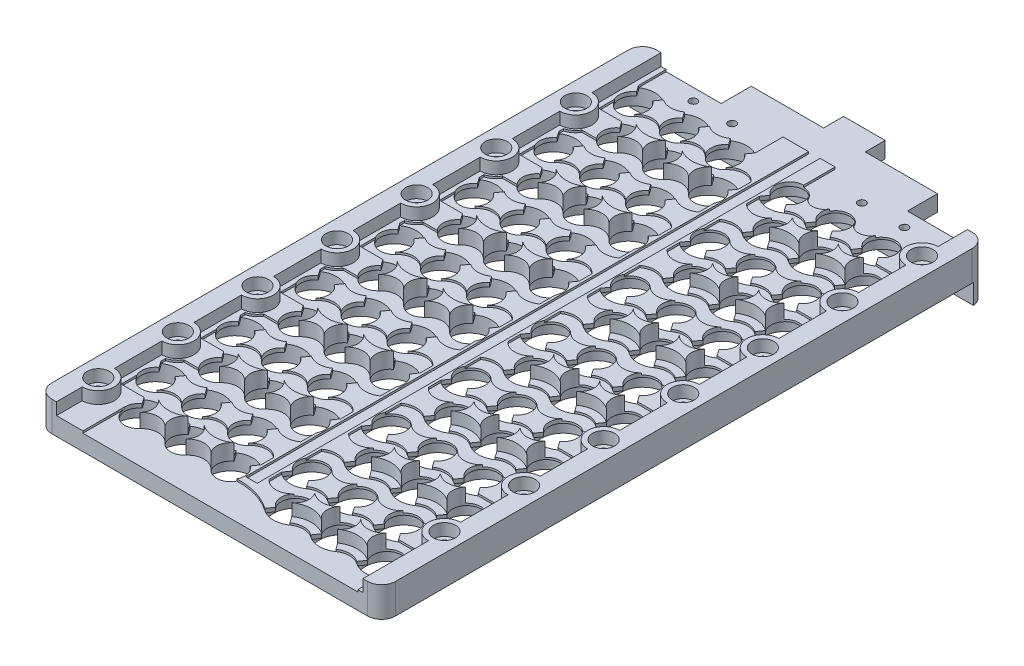
SolidWorks part; units mm, degrees
material "Nylon 6/10"
ref_plane "Front Plane" through (0, 0, 0) normal (0, 0, 1) x (1, 0, 0)
ref_plane "Top Plane" through (0, 0, 0) normal (0, 1, 0) x (1, 0, 0)
ref_plane "Right Plane" through (0, 0, 0) normal (1, 0, 0) x (0, 0, -1)
sketch "Sketch2" plane through (0, 0, 0) normal (0, 1, 0) x (1, 0, 0)
  line L1 (0, 0) -> (171.7, 0)
  line L2 (0, 0) -> (0, 295.6287)
  line L3 (0, 295.6287) -> (171.7, 295.6287)
  line L4 (171.7, 0) -> (171.7, 295.6287)
  dimension "D1" = 171.7
  dimension "D2" = 295.6287
extrude "Boss-Extrude6" add sketch "Sketch2" along normal blind 9
sketch "Sketch1" plane through (0, 0, 0) normal (0, 1, 0) x (1, 0, 0)
  line L1 (0, 0) -> (171.7029, 0)
  line L2 (0, 0) -> (0, 295.6287)
  line L3 (0, 295.6287) -> (171.7029, 295.6287)
  line L4 (171.7029, 0) -> (171.7029, 295.6287)
  line L5 (29.5647, 20.875) -> (18.0897, 40.7503) construction
  line L6 (18.0897, 40.7503) -> (18.0897, 20.875) construction
  line L7 (18.0897, 20.875) -> (29.5647, 20.875) construction
  line L8 (29.5647, 60.6256) -> (18.0897, 40.7503) construction
  line L9 (18.0897, 40.7503) -> (29.5647, 40.7503) construction
  line L10 (29.5647, 40.7503) -> (29.5647, 60.6256) construction
  line L11 (29.5647, 60.6256) -> (0, 60.6256) construction
  line L12 (0, 60.6256) -> (18.0897, 80.5008) construction
  line L13 (142.1382, 40.7503) -> (171.7029, 40.7503) construction
  line L14 (171.7029, 40.7503) -> (153.6132, 20.875) construction
  circle A1 centre (29.5647, 20.875) radius 10.875
  circle A2 centre (18.0897, 40.7503) radius 10.875
  circle A3 centre (41.0397, 40.7503) radius 10.875
  circle A4 centre (52.5147, 20.875) radius 10.875
  circle A5 centre (63.9897, 40.7503) radius 10.875
  circle A6 centre (75.4647, 20.875) radius 10.875
  circle A43 centre (96.2382, 40.7503) radius 10.875
  circle A44 centre (119.1882, 40.7503) radius 10.875
  circle A45 centre (142.1382, 40.7503) radius 10.875
  circle A46 centre (153.6132, 20.875) radius 10.875
  circle A47 centre (130.6632, 20.875) radius 10.875
  circle A48 centre (107.7132, 20.875) radius 10.875
  circle A49 centre (96.2382, 80.5008) radius 10.875
  circle A50 centre (119.1882, 80.5008) radius 10.875
  circle A51 centre (142.1382, 80.5008) radius 10.875
  circle A52 centre (153.6132, 60.6256) radius 10.875
  circle A53 centre (130.6632, 60.6256) radius 10.875
  circle A54 centre (107.7132, 60.6256) radius 10.875
  circle A55 centre (96.2382, 120.2514) radius 10.875
  circle A56 centre (119.1882, 120.2514) radius 10.875
  circle A57 centre (142.1382, 120.2514) radius 10.875
  circle A58 centre (153.6132, 100.3761) radius 10.875
  circle A59 centre (130.6632, 100.3761) radius 10.875
  circle A60 centre (107.7132, 100.3761) radius 10.875
  circle A61 centre (96.2382, 160.002) radius 10.875
  circle A62 centre (119.1882, 160.002) radius 10.875
  circle A63 centre (142.1382, 160.002) radius 10.875
  circle A64 centre (153.6132, 140.1267) radius 10.875
  circle A65 centre (130.6632, 140.1267) radius 10.875
  circle A66 centre (107.7132, 140.1267) radius 10.875
  circle A67 centre (96.2382, 199.7525) radius 10.875
  circle A68 centre (119.1882, 199.7525) radius 10.875
  circle A69 centre (142.1382, 199.7525) radius 10.875
  circle A70 centre (153.6132, 179.8773) radius 10.875
  circle A71 centre (130.6632, 179.8773) radius 10.875
  circle A72 centre (107.7132, 179.8773) radius 10.875
  circle A73 centre (96.2382, 239.5031) radius 10.875
  circle A74 centre (119.1882, 239.5031) radius 10.875
  circle A75 centre (142.1382, 239.5031) radius 10.875
  circle A76 centre (153.6132, 219.6278) radius 10.875
  circle A77 centre (130.6632, 219.6278) radius 10.875
  circle A78 centre (107.7132, 219.6278) radius 10.875
  circle A79 centre (96.2382, 279.2537) radius 10.875
  circle A80 centre (119.1882, 279.2537) radius 10.875
  circle A81 centre (142.1382, 279.2537) radius 10.875
  circle A82 centre (153.6132, 259.3784) radius 10.875
  circle A83 centre (130.6632, 259.3784) radius 10.875
  circle A84 centre (107.7132, 259.3784) radius 10.875
  circle A127 centre (18.0897, 80.5008) radius 10.875
  circle A128 centre (41.0397, 80.5008) radius 10.875
  circle A129 centre (63.9897, 80.5008) radius 10.875
  circle A130 centre (75.4647, 60.6256) radius 10.875
  circle A131 centre (52.5147, 60.6256) radius 10.875
  circle A132 centre (29.5647, 60.6256) radius 10.875
  circle A133 centre (18.0897, 120.2514) radius 10.875
  circle A134 centre (41.0397, 120.2514) radius 10.875
  circle A135 centre (63.9897, 120.2514) radius 10.875
  circle A136 centre (75.4647, 100.3761) radius 10.875
  circle A137 centre (52.5147, 100.3761) radius 10.875
  circle A138 centre (29.5647, 100.3761) radius 10.875
  circle A139 centre (18.0897, 160.002) radius 10.875
  circle A140 centre (41.0397, 160.002) radius 10.875
  circle A141 centre (63.9897, 160.002) radius 10.875
  circle A142 centre (75.4647, 140.1267) radius 10.875
  circle A143 centre (52.5147, 140.1267) radius 10.875
  circle A144 centre (29.5647, 140.1267) radius 10.875
  circle A145 centre (18.0897, 199.7525) radius 10.875
  circle A146 centre (41.0397, 199.7525) radius 10.875
  circle A147 centre (63.9897, 199.7525) radius 10.875
  circle A148 centre (75.4647, 179.8773) radius 10.875
  circle A149 centre (52.5147, 179.8773) radius 10.875
  circle A150 centre (29.5647, 179.8773) radius 10.875
  circle A151 centre (18.0897, 239.5031) radius 10.875
  circle A152 centre (41.0397, 239.5031) radius 10.875
  circle A153 centre (63.9897, 239.5031) radius 10.875
  circle A154 centre (75.4647, 219.6278) radius 10.875
  circle A155 centre (52.5147, 219.6278) radius 10.875
  circle A156 centre (29.5647, 219.6278) radius 10.875
  circle A157 centre (18.0897, 279.2537) radius 10.875
  circle A158 centre (41.0397, 279.2537) radius 10.875
  circle A159 centre (63.9897, 279.2537) radius 10.875
  circle A160 centre (75.4647, 259.3784) radius 10.875
  circle A161 centre (52.5147, 259.3784) radius 10.875
  circle A162 centre (29.5647, 259.3784) radius 10.875
  dimension "D1" = 21.75
  dimension "D2" = 20.875
  dimension "D3" = 22.95
  dimension "D5" = 60
  dimension "D8" = 22.95
  dimension "D9" = 22.95
  dimension "D10" = 60
  dimension "D13" = 28.75
  dimension "D4" = 16.375
  dimension "D16" = 26.875
  dimension "D14" = 26.875
  dimension "D6" = 3
  dimension "D7" = 1
  dimension "D11" = 2
  dimension "D12" = 7
extrude "Cut-Extrude1" cut sketch "Sketch1" along normal blind 7 contours A47 | A46 | A45 | A44 | A43 | A54 | A53 | A52 | A51 | A50 | A49 | A60 | A59 | A58 | A57 | A56 | A55 | A66 | A65 | A64 | A63 | A62 | A61 | A72 | A67 | A78 | A73 | A84 | A79 | A80 | A81 | A82 | A83 | A74 | A75 | A77 | A76 | A69 | A70 | A71 | A68 | A159 | A158 | A157 | A162 | A161 | A160 | A153 | A152 | A156 | A151 | A155 | A154 | A147 | A146 | A145 | A148 | A141 | A149 | A150 | A140 | A142 | A143 | A144 | A139 | A133 | A134 | A135 | A136 | A137 | A138 | A128 | A127 | A129 | A130 | A131 | A132 | A2 | A3 | A5 | A6 | A4 | A1 | A48 | A130 region at (29.5647, 0, -20.875) region at (18.0897, 0, -40.7503) region at (41.0397, 0, -40.7503) region at (52.5147, 0, -20.875) region at (63.9897, 0, -40.7503) region at (75.4647, 0, -20.875) region at (96.2382, 0, -40.7503) region at (119.1882, 0, -40.7503) region at (142.1382, 0, -40.7503) region at (153.6132, 0, -20.875) region at (130.6632, 0, -20.875) region at (96.2382, 0, -80.5008) region at (119.1882, 0, -80.5008) region at (142.1382, 0, -80.5008) region at (153.6132, 0, -60.6256) region at (130.6632, 0, -60.6256) region at (107.7132, 0, -60.6256) region at (96.2382, 0, -120.2514) region at (119.1882, 0, -120.2514) region at (142.1382, 0, -120.2514) region at (153.6132, 0, -100.3761) region at (130.6632, 0, -100.3761) region at (107.7132, 0, -100.3761) region at (96.2382, 0, -160.002) region at (119.1882, 0, -160.002) region at (142.1382, 0, -160.002) region at (153.6132, 0, -140.1267) region at (130.6632, 0, -140.1267) region at (107.7132, 0, -140.1267) region at (96.2382, 0, -199.7525) region at (119.1882, 0, -199.7525) region at (142.1382, 0, -199.7525) region at (153.6132, 0, -179.8773) region at (130.6632, 0, -179.8773) region at (107.7132, 0, -179.8773) region at (96.2382, 0, -239.5031) region at (119.1882, 0, -239.5031) region at (142.1382, 0, -239.5031) region at (153.6132, 0, -219.6278) region at (130.6632, 0, -219.6278) region at (107.7132, 0, -219.6278) region at (96.2382, 0, -279.2537) region at (119.1882, 0, -279.2537) region at (142.1382, 0, -279.2537) region at (153.6132, 0, -259.3784) region at (130.6632, 0, -259.3784) region at (107.7132, 0, -259.3784) region at (18.0897, 0, -80.5008) region at (41.0397, 0, -80.5008) region at (63.9897, 0, -80.5008) region at (75.4647, 0, -60.6256) region at (52.5147, 0, -60.6256) region at (29.5647, 0, -60.6256) region at (18.0897, 0, -120.2514) region at (41.0397, 0, -120.2514) region at (63.9897, 0, -120.2514) region at (75.4647, 0, -100.3761) region at (52.5147, 0, -100.3761) region at (29.5647, 0, -100.3761) region at (18.0897, 0, -160.002)
sketch "Sketch3" plane through (0, 0, 0) normal (0, -1, 0) x (1, 0, 0)
  line L0 (18.0897, -279.2537) -> (18.0897, -290.1287) construction
  line L1 (11.8521, -288.162) -> (18.0897, -279.2537) construction
  line L2 (18.0897, -279.2537) -> (24.3274, -288.162) construction
  line L3 (22.1048, -284.9877) -> (24.3274, -288.162)
  line L4 (14.0747, -284.9877) -> (11.8521, -288.162)
  line L5 (18.0897, -279.2537) -> (28.9647, -279.2537) construction
  line L6 (29.5647, -259.3784) -> (29.5647, -270.2534) construction
  line L7 (23.3271, -268.2867) -> (29.5647, -259.3784) construction
  line L8 (29.5647, -259.3784) -> (35.8024, -268.2867) construction
  line L9 (33.5798, -265.1125) -> (35.8024, -268.2867)
  line L10 (25.5497, -265.1125) -> (23.3271, -268.2867)
  line L11 (29.5647, -259.3784) -> (40.4397, -259.3784) construction
  line L12 (56.5298, -265.1125) -> (58.7524, -268.2867)
  line L13 (48.4997, -265.1125) -> (46.2771, -268.2867)
  line L14 (45.0548, -284.9877) -> (47.2774, -288.162)
  line L15 (37.0247, -284.9877) -> (34.8021, -288.162)
  line L16 (79.4798, -265.1125) -> (81.7024, -268.2867)
  line L17 (71.4497, -265.1125) -> (69.2271, -268.2867)
  line L18 (68.0048, -284.9877) -> (70.2274, -288.162)
  line L19 (59.9747, -284.9877) -> (57.7521, -288.162)
  line L178 (100.2532, -273.5196) -> (102.4758, -270.3454)
  line L181 (92.2231, -273.5196) -> (90.0005, -270.3454)
  line L182 (96.2382, -279.2537) -> (103.2382, -279.2537) construction
  line L183 (96.2382, -279.2537) -> (96.2382, -268.3787) construction
  line L184 (96.2382, -279.2537) -> (102.4758, -270.3454) construction
  line L186 (96.2382, -279.2537) -> (90.0005, -270.3454) construction
  line L187 (111.7282, -253.6443) -> (113.9508, -250.4701)
  line L188 (103.6981, -253.6443) -> (101.4755, -250.4701)
  line L189 (107.7132, -259.3784) -> (114.7132, -259.3784) construction
  line L190 (107.7132, -259.3784) -> (107.7132, -248.5034) construction
  line L191 (107.7132, -259.3784) -> (113.9508, -250.4701) construction
  line L192 (107.7132, -259.3784) -> (101.4755, -250.4701) construction
  line L193 (33.5798, -225.3619) -> (35.8024, -228.5361)
  line L194 (25.5497, -225.3619) -> (23.3271, -228.5361)
  line L195 (22.1048, -245.2372) -> (24.3274, -248.4114)
  line L196 (14.0747, -245.2372) -> (11.8521, -248.4114)
  line L197 (56.5298, -225.3619) -> (58.7524, -228.5361)
  line L198 (48.4997, -225.3619) -> (46.2771, -228.5361)
  line L199 (45.0548, -245.2372) -> (47.2774, -248.4114)
  line L200 (37.0247, -245.2372) -> (34.8021, -248.4114)
  line L201 (79.4798, -225.3619) -> (81.7024, -228.5361)
  line L202 (71.4497, -225.3619) -> (69.2271, -228.5361)
  line L203 (68.0048, -245.2372) -> (70.2274, -248.4114)
  line L204 (59.9747, -245.2372) -> (57.7521, -248.4114)
  line L205 (33.5798, -185.6113) -> (35.8024, -188.7855)
  line L206 (25.5497, -185.6113) -> (23.3271, -188.7855)
  line L207 (22.1048, -205.4866) -> (24.3274, -208.6608)
  line L208 (14.0747, -205.4866) -> (11.8521, -208.6608)
  line L209 (56.5298, -185.6113) -> (58.7524, -188.7855)
  line L210 (48.4997, -185.6113) -> (46.2771, -188.7855)
  line L211 (45.0548, -205.4866) -> (47.2774, -208.6608)
  line L212 (37.0247, -205.4866) -> (34.8021, -208.6608)
  line L213 (79.4798, -185.6113) -> (81.7024, -188.7855)
  line L214 (71.4497, -185.6113) -> (69.2271, -188.7855)
  line L215 (68.0048, -205.4866) -> (70.2274, -208.6608)
  line L216 (59.9747, -205.4866) -> (57.7521, -208.6608)
  line L217 (33.5798, -145.8608) -> (35.8024, -149.035)
  line L218 (25.5497, -145.8608) -> (23.3271, -149.035)
  line L219 (22.1048, -165.736) -> (24.3274, -168.9103)
  line L220 (14.0747, -165.736) -> (11.8521, -168.9103)
  line L221 (56.5298, -145.8608) -> (58.7524, -149.035)
  line L222 (48.4997, -145.8608) -> (46.2771, -149.035)
  line L223 (45.0548, -165.736) -> (47.2774, -168.9103)
  line L224 (37.0247, -165.736) -> (34.8021, -168.9103)
  line L225 (79.4798, -145.8608) -> (81.7024, -149.035)
  line L226 (71.4497, -145.8608) -> (69.2271, -149.035)
  line L227 (68.0048, -165.736) -> (70.2274, -168.9103)
  line L228 (59.9747, -165.736) -> (57.7521, -168.9103)
  line L229 (33.5798, -106.1102) -> (35.8024, -109.2844)
  line L230 (25.5497, -106.1102) -> (23.3271, -109.2844)
  line L231 (22.1048, -125.9855) -> (24.3274, -129.1597)
  line L232 (14.0747, -125.9855) -> (11.8521, -129.1597)
  line L233 (56.5298, -106.1102) -> (58.7524, -109.2844)
  line L234 (48.4997, -106.1102) -> (46.2771, -109.2844)
  line L235 (45.0548, -125.9855) -> (47.2774, -129.1597)
  line L236 (37.0247, -125.9855) -> (34.8021, -129.1597)
  line L237 (79.4798, -106.1102) -> (81.7024, -109.2844)
  line L238 (71.4497, -106.1102) -> (69.2271, -109.2844)
  line L239 (68.0048, -125.9855) -> (70.2274, -129.1597)
  line L240 (59.9747, -125.9855) -> (57.7521, -129.1597)
  line L241 (33.5798, -66.3596) -> (35.8024, -69.5338)
  line L242 (25.5497, -66.3596) -> (23.3271, -69.5338)
  line L243 (22.1048, -86.2349) -> (24.3274, -89.4091)
  line L244 (14.0747, -86.2349) -> (11.8521, -89.4091)
  line L245 (56.5298, -66.3596) -> (58.7524, -69.5338)
  line L246 (48.4997, -66.3596) -> (46.2771, -69.5338)
  line L247 (45.0548, -86.2349) -> (47.2774, -89.4091)
  line L248 (37.0247, -86.2349) -> (34.8021, -89.4091)
  line L249 (79.4798, -66.3596) -> (81.7024, -69.5338)
  line L250 (71.4497, -66.3596) -> (69.2271, -69.5338)
  line L251 (68.0048, -86.2349) -> (70.2274, -89.4091)
  line L252 (59.9747, -86.2349) -> (57.7521, -89.4091)
  line L253 (33.5798, -26.6091) -> (35.8024, -29.7833)
  line L254 (25.5497, -26.6091) -> (23.3271, -29.7833)
  line L255 (22.1048, -46.4843) -> (24.3274, -49.6586)
  line L256 (14.0747, -46.4843) -> (11.8521, -49.6586)
  line L257 (56.5298, -26.6091) -> (58.7524, -29.7833)
  line L258 (48.4997, -26.6091) -> (46.2771, -29.7833)
  line L259 (45.0548, -46.4843) -> (47.2774, -49.6586)
  line L260 (37.0247, -46.4843) -> (34.8021, -49.6586)
  line L261 (79.4798, -26.6091) -> (81.7024, -29.7833)
  line L262 (71.4497, -26.6091) -> (69.2271, -29.7833)
  line L263 (68.0048, -46.4843) -> (70.2274, -49.6586)
  line L264 (59.9747, -46.4843) -> (57.7521, -49.6586)
  line L265 (123.2032, -273.5196) -> (125.4258, -270.3454)
  line L266 (115.1731, -273.5196) -> (112.9505, -270.3454)
  line L267 (134.6782, -253.6443) -> (136.9008, -250.4701)
  line L268 (126.6481, -253.6443) -> (124.4255, -250.4701)
  line L269 (146.1532, -273.5196) -> (148.3758, -270.3454)
  line L270 (138.1231, -273.5196) -> (135.9005, -270.3454)
  line L271 (157.6282, -253.6443) -> (159.8508, -250.4701)
  line L272 (149.5981, -253.6443) -> (147.3755, -250.4701)
  line L273 (123.2032, -233.769) -> (125.4258, -230.5948)
  line L274 (115.1731, -233.769) -> (112.9505, -230.5948)
  line L275 (134.6782, -213.8938) -> (136.9008, -210.7196)
  line L276 (126.6481, -213.8938) -> (124.4255, -210.7196)
  line L277 (146.1532, -233.769) -> (148.3758, -230.5948)
  line L278 (138.1231, -233.769) -> (135.9005, -230.5948)
  line L279 (157.6282, -213.8938) -> (159.8508, -210.7196)
  line L280 (149.5981, -213.8938) -> (147.3755, -210.7196)
  line L281 (123.2032, -194.0185) -> (125.4258, -190.8443)
  line L282 (115.1731, -194.0185) -> (112.9505, -190.8443)
  line L283 (134.6782, -174.1432) -> (136.9008, -170.969)
  line L284 (126.6481, -174.1432) -> (124.4255, -170.969)
  line L285 (146.1532, -194.0185) -> (148.3758, -190.8443)
  line L286 (138.1231, -194.0185) -> (135.9005, -190.8443)
  line L287 (157.6282, -174.1432) -> (159.8508, -170.969)
  line L288 (149.5981, -174.1432) -> (147.3755, -170.969)
  line L289 (123.2032, -154.2679) -> (125.4258, -151.0937)
  line L290 (115.1731, -154.2679) -> (112.9505, -151.0937)
  line L291 (134.6782, -134.3926) -> (136.9008, -131.2184)
  line L292 (126.6481, -134.3926) -> (124.4255, -131.2184)
  line L293 (146.1532, -154.2679) -> (148.3758, -151.0937)
  line L294 (138.1231, -154.2679) -> (135.9005, -151.0937)
  line L295 (157.6282, -134.3926) -> (159.8508, -131.2184)
  line L296 (149.5981, -134.3926) -> (147.3755, -131.2184)
  line L297 (123.2032, -114.5174) -> (125.4258, -111.3431)
  line L298 (115.1731, -114.5174) -> (112.9505, -111.3431)
  line L299 (134.6782, -94.6421) -> (136.9008, -91.4679)
  line L300 (126.6481, -94.6421) -> (124.4255, -91.4679)
  line L301 (146.1532, -114.5174) -> (148.3758, -111.3431)
  line L302 (138.1231, -114.5174) -> (135.9005, -111.3431)
  line L303 (157.6282, -94.6421) -> (159.8508, -91.4679)
  line L304 (149.5981, -94.6421) -> (147.3755, -91.4679)
  line L305 (123.2032, -74.7668) -> (125.4258, -71.5926)
  line L306 (115.1731, -74.7668) -> (112.9505, -71.5926)
  line L307 (134.6782, -54.8915) -> (136.9008, -51.7173)
  line L308 (126.6481, -54.8915) -> (124.4255, -51.7173)
  line L309 (146.1532, -74.7668) -> (148.3758, -71.5926)
  line L310 (138.1231, -74.7668) -> (135.9005, -71.5926)
  line L311 (157.6282, -54.8915) -> (159.8508, -51.7173)
  line L312 (149.5981, -54.8915) -> (147.3755, -51.7173)
  line L313 (123.2032, -35.0162) -> (125.4258, -31.842)
  line L314 (115.1731, -35.0162) -> (112.9505, -31.842)
  line L315 (134.6782, -15.1409) -> (136.9008, -11.9667)
  line L316 (126.6481, -15.1409) -> (124.4255, -11.9667)
  line L317 (146.1532, -35.0162) -> (148.3758, -31.842)
  line L318 (138.1231, -35.0162) -> (135.9005, -31.842)
  line L319 (157.6282, -15.1409) -> (159.8508, -11.9667)
  line L320 (149.5981, -15.1409) -> (147.3755, -11.9667)
  line L321 (100.2532, -233.769) -> (102.4758, -230.5948)
  line L322 (92.2231, -233.769) -> (90.0005, -230.5948)
  line L323 (111.7282, -213.8938) -> (113.9508, -210.7196)
  line L324 (103.6981, -213.8938) -> (101.4755, -210.7196)
  line L325 (100.2532, -194.0185) -> (102.4758, -190.8443)
  line L326 (92.2231, -194.0185) -> (90.0005, -190.8443)
  line L327 (111.7282, -174.1432) -> (113.9508, -170.969)
  line L328 (103.6981, -174.1432) -> (101.4755, -170.969)
  line L329 (100.2532, -154.2679) -> (102.4758, -151.0937)
  line L330 (92.2231, -154.2679) -> (90.0005, -151.0937)
  line L331 (111.7282, -134.3926) -> (113.9508, -131.2184)
  line L332 (103.6981, -134.3926) -> (101.4755, -131.2184)
  line L333 (100.2532, -114.5174) -> (102.4758, -111.3431)
  line L334 (92.2231, -114.5174) -> (90.0005, -111.3431)
  line L335 (111.7282, -94.6421) -> (113.9508, -91.4679)
  line L336 (103.6981, -94.6421) -> (101.4755, -91.4679)
  line L337 (100.2532, -74.7668) -> (102.4758, -71.5926)
  line L338 (92.2231, -74.7668) -> (90.0005, -71.5926)
  line L339 (111.7282, -54.8915) -> (113.9508, -51.7173)
  line L340 (103.6981, -54.8915) -> (101.4755, -51.7173)
  line L341 (100.2532, -35.0162) -> (102.4758, -31.842)
  line L342 (92.2231, -35.0162) -> (90.0005, -31.842)
  line L343 (111.7282, -15.1409) -> (113.9508, -11.9667)
  line L344 (103.6981, -15.1409) -> (101.4755, -11.9667)
  arc A0 (14.0747, -284.9877) -> (22.1048, -284.9877) centre (18.0897, -279.2537) cw
  arc A1 (11.8521, -288.162) -> (24.3274, -288.162) centre (18.0897, -279.2537) ccw
  circle A2 centre (18.0897, -279.2537) radius 10.875 construction
  circle A3 centre (18.0897, -279.2537) radius 10.875 construction
  arc A4 (25.5497, -265.1125) -> (33.5798, -265.1125) centre (29.5647, -259.3784) cw
  arc A5 (23.3271, -268.2867) -> (35.8024, -268.2867) centre (29.5647, -259.3784) ccw
  circle A7 centre (29.5647, -259.3784) radius 10.875 construction
  circle A8 centre (29.5647, -259.3784) radius 10.875 construction
  arc A9 (46.2771, -268.2867) -> (58.7524, -268.2867) centre (52.5147, -259.3784) ccw
  arc A10 (48.4997, -265.1125) -> (56.5298, -265.1125) centre (52.5147, -259.3784) cw
  arc A11 (34.8021, -288.162) -> (47.2774, -288.162) centre (41.0397, -279.2537) ccw
  arc A12 (37.0247, -284.9877) -> (45.0548, -284.9877) centre (41.0397, -279.2537) cw
  arc A13 (69.2271, -268.2867) -> (81.7024, -268.2867) centre (75.4647, -259.3784) ccw
  arc A14 (71.4497, -265.1125) -> (79.4798, -265.1125) centre (75.4647, -259.3784) cw
  arc A15 (57.7521, -288.162) -> (70.2274, -288.162) centre (63.9897, -279.2537) ccw
  arc A16 (59.9747, -284.9877) -> (68.0048, -284.9877) centre (63.9897, -279.2537) cw
  circle A18 centre (41.0397, -279.2537) radius 10.875 construction
  arc A177 (101.4755, -250.4701) -> (113.9508, -250.4701) centre (107.7132, -259.3784) cw
  arc A178 (103.6981, -253.6443) -> (111.7282, -253.6443) centre (107.7132, -259.3784) ccw
  arc A181 (90.0005, -270.3454) -> (102.4758, -270.3454) centre (96.2382, -279.2537) cw
  circle A182 centre (107.7132, -259.3784) radius 10.875 construction
  arc A183 (23.3271, -228.5361) -> (35.8024, -228.5361) centre (29.5647, -219.6278) ccw
  arc A184 (92.2231, -273.5196) -> (100.2532, -273.5196) centre (96.2382, -279.2537) ccw
  circle A185 centre (96.2382, -279.2537) radius 10.875 construction
  arc A186 (25.5497, -225.3619) -> (33.5798, -225.3619) centre (29.5647, -219.6278) cw
  arc A187 (11.8521, -248.4114) -> (24.3274, -248.4114) centre (18.0897, -239.5031) ccw
  arc A188 (14.0747, -245.2372) -> (22.1048, -245.2372) centre (18.0897, -239.5031) cw
  arc A189 (46.2771, -228.5361) -> (58.7524, -228.5361) centre (52.5147, -219.6278) ccw
  arc A190 (48.4997, -225.3619) -> (56.5298, -225.3619) centre (52.5147, -219.6278) cw
  arc A191 (34.8021, -248.4114) -> (47.2774, -248.4114) centre (41.0397, -239.5031) ccw
  arc A192 (37.0247, -245.2372) -> (45.0548, -245.2372) centre (41.0397, -239.5031) cw
  arc A193 (69.2271, -228.5361) -> (81.7024, -228.5361) centre (75.4647, -219.6278) ccw
  arc A194 (71.4497, -225.3619) -> (79.4798, -225.3619) centre (75.4647, -219.6278) cw
  arc A195 (57.7521, -248.4114) -> (70.2274, -248.4114) centre (63.9897, -239.5031) ccw
  arc A196 (59.9747, -245.2372) -> (68.0048, -245.2372) centre (63.9897, -239.5031) cw
  arc A197 (23.3271, -188.7855) -> (35.8024, -188.7855) centre (29.5647, -179.8773) ccw
  arc A198 (25.5497, -185.6113) -> (33.5798, -185.6113) centre (29.5647, -179.8773) cw
  arc A199 (11.8521, -208.6608) -> (24.3274, -208.6608) centre (18.0897, -199.7525) ccw
  arc A200 (14.0747, -205.4866) -> (22.1048, -205.4866) centre (18.0897, -199.7525) cw
  arc A201 (46.2771, -188.7855) -> (58.7524, -188.7855) centre (52.5147, -179.8773) ccw
  arc A202 (48.4997, -185.6113) -> (56.5298, -185.6113) centre (52.5147, -179.8773) cw
  arc A203 (34.8021, -208.6608) -> (47.2774, -208.6608) centre (41.0397, -199.7525) ccw
  arc A204 (37.0247, -205.4866) -> (45.0548, -205.4866) centre (41.0397, -199.7525) cw
  arc A205 (69.2271, -188.7855) -> (81.7024, -188.7855) centre (75.4647, -179.8773) ccw
  arc A206 (71.4497, -185.6113) -> (79.4798, -185.6113) centre (75.4647, -179.8773) cw
  arc A207 (57.7521, -208.6608) -> (70.2274, -208.6608) centre (63.9897, -199.7525) ccw
  arc A208 (59.9747, -205.4866) -> (68.0048, -205.4866) centre (63.9897, -199.7525) cw
  arc A209 (23.3271, -149.035) -> (35.8024, -149.035) centre (29.5647, -140.1267) ccw
  arc A210 (25.5497, -145.8608) -> (33.5798, -145.8608) centre (29.5647, -140.1267) cw
  arc A211 (11.8521, -168.9103) -> (24.3274, -168.9103) centre (18.0897, -160.002) ccw
  arc A212 (14.0747, -165.736) -> (22.1048, -165.736) centre (18.0897, -160.002) cw
  arc A213 (46.2771, -149.035) -> (58.7524, -149.035) centre (52.5147, -140.1267) ccw
  arc A214 (48.4997, -145.8608) -> (56.5298, -145.8608) centre (52.5147, -140.1267) cw
  arc A215 (34.8021, -168.9103) -> (47.2774, -168.9103) centre (41.0397, -160.002) ccw
  arc A216 (37.0247, -165.736) -> (45.0548, -165.736) centre (41.0397, -160.002) cw
  arc A217 (69.2271, -149.035) -> (81.7024, -149.035) centre (75.4647, -140.1267) ccw
  arc A218 (71.4497, -145.8608) -> (79.4798, -145.8608) centre (75.4647, -140.1267) cw
  arc A219 (57.7521, -168.9103) -> (70.2274, -168.9103) centre (63.9897, -160.002) ccw
  arc A220 (59.9747, -165.736) -> (68.0048, -165.736) centre (63.9897, -160.002) cw
  arc A221 (23.3271, -109.2844) -> (35.8024, -109.2844) centre (29.5647, -100.3761) ccw
  arc A222 (25.5497, -106.1102) -> (33.5798, -106.1102) centre (29.5647, -100.3761) cw
  arc A223 (11.8521, -129.1597) -> (24.3274, -129.1597) centre (18.0897, -120.2514) ccw
  arc A224 (14.0747, -125.9855) -> (22.1048, -125.9855) centre (18.0897, -120.2514) cw
  arc A225 (46.2771, -109.2844) -> (58.7524, -109.2844) centre (52.5147, -100.3761) ccw
  arc A226 (48.4997, -106.1102) -> (56.5298, -106.1102) centre (52.5147, -100.3761) cw
  arc A227 (34.8021, -129.1597) -> (47.2774, -129.1597) centre (41.0397, -120.2514) ccw
  arc A228 (37.0247, -125.9855) -> (45.0548, -125.9855) centre (41.0397, -120.2514) cw
  arc A229 (69.2271, -109.2844) -> (81.7024, -109.2844) centre (75.4647, -100.3761) ccw
  arc A230 (71.4497, -106.1102) -> (79.4798, -106.1102) centre (75.4647, -100.3761) cw
  arc A231 (57.7521, -129.1597) -> (70.2274, -129.1597) centre (63.9897, -120.2514) ccw
  arc A232 (59.9747, -125.9855) -> (68.0048, -125.9855) centre (63.9897, -120.2514) cw
  arc A233 (23.3271, -69.5338) -> (35.8024, -69.5338) centre (29.5647, -60.6256) ccw
  arc A234 (25.5497, -66.3596) -> (33.5798, -66.3596) centre (29.5647, -60.6256) cw
  arc A235 (11.8521, -89.4091) -> (24.3274, -89.4091) centre (18.0897, -80.5008) ccw
  arc A236 (14.0747, -86.2349) -> (22.1048, -86.2349) centre (18.0897, -80.5008) cw
  arc A237 (46.2771, -69.5338) -> (58.7524, -69.5338) centre (52.5147, -60.6256) ccw
  arc A238 (48.4997, -66.3596) -> (56.5298, -66.3596) centre (52.5147, -60.6256) cw
  arc A239 (34.8021, -89.4091) -> (47.2774, -89.4091) centre (41.0397, -80.5008) ccw
  arc A240 (37.0247, -86.2349) -> (45.0548, -86.2349) centre (41.0397, -80.5008) cw
  arc A241 (69.2271, -69.5338) -> (81.7024, -69.5338) centre (75.4647, -60.6256) ccw
  arc A242 (71.4497, -66.3596) -> (79.4798, -66.3596) centre (75.4647, -60.6256) cw
  arc A243 (57.7521, -89.4091) -> (70.2274, -89.4091) centre (63.9897, -80.5008) ccw
  arc A244 (59.9747, -86.2349) -> (68.0048, -86.2349) centre (63.9897, -80.5008) cw
  arc A245 (23.3271, -29.7833) -> (35.8024, -29.7833) centre (29.5647, -20.875) ccw
  arc A246 (25.5497, -26.6091) -> (33.5798, -26.6091) centre (29.5647, -20.875) cw
  arc A247 (11.8521, -49.6586) -> (24.3274, -49.6586) centre (18.0897, -40.7503) ccw
  arc A248 (14.0747, -46.4843) -> (22.1048, -46.4843) centre (18.0897, -40.7503) cw
  arc A249 (46.2771, -29.7833) -> (58.7524, -29.7833) centre (52.5147, -20.875) ccw
  arc A250 (48.4997, -26.6091) -> (56.5298, -26.6091) centre (52.5147, -20.875) cw
  arc A251 (34.8021, -49.6586) -> (47.2774, -49.6586) centre (41.0397, -40.7503) ccw
  arc A252 (37.0247, -46.4843) -> (45.0548, -46.4843) centre (41.0397, -40.7503) cw
  arc A253 (69.2271, -29.7833) -> (81.7024, -29.7833) centre (75.4647, -20.875) ccw
  arc A254 (71.4497, -26.6091) -> (79.4798, -26.6091) centre (75.4647, -20.875) cw
  arc A255 (57.7521, -49.6586) -> (70.2274, -49.6586) centre (63.9897, -40.7503) ccw
  arc A256 (59.9747, -46.4843) -> (68.0048, -46.4843) centre (63.9897, -40.7503) cw
  arc A257 (112.9505, -270.3454) -> (125.4258, -270.3454) centre (119.1882, -279.2537) cw
  arc A258 (115.1731, -273.5196) -> (123.2032, -273.5196) centre (119.1882, -279.2537) ccw
  arc A259 (124.4255, -250.4701) -> (136.9008, -250.4701) centre (130.6632, -259.3784) cw
  arc A260 (126.6481, -253.6443) -> (134.6782, -253.6443) centre (130.6632, -259.3784) ccw
  arc A261 (135.9005, -270.3454) -> (148.3758, -270.3454) centre (142.1382, -279.2537) cw
  arc A262 (138.1231, -273.5196) -> (146.1532, -273.5196) centre (142.1382, -279.2537) ccw
  arc A263 (147.3755, -250.4701) -> (159.8508, -250.4701) centre (153.6132, -259.3784) cw
  arc A264 (149.5981, -253.6443) -> (157.6282, -253.6443) centre (153.6132, -259.3784) ccw
  arc A265 (112.9505, -230.5948) -> (125.4258, -230.5948) centre (119.1882, -239.5031) cw
  arc A266 (115.1731, -233.769) -> (123.2032, -233.769) centre (119.1882, -239.5031) ccw
  arc A267 (124.4255, -210.7196) -> (136.9008, -210.7196) centre (130.6632, -219.6278) cw
  arc A268 (126.6481, -213.8938) -> (134.6782, -213.8938) centre (130.6632, -219.6278) ccw
  arc A269 (135.9005, -230.5948) -> (148.3758, -230.5948) centre (142.1382, -239.5031) cw
  arc A270 (138.1231, -233.769) -> (146.1532, -233.769) centre (142.1382, -239.5031) ccw
  arc A271 (147.3755, -210.7196) -> (159.8508, -210.7196) centre (153.6132, -219.6278) cw
  arc A272 (149.5981, -213.8938) -> (157.6282, -213.8938) centre (153.6132, -219.6278) ccw
  arc A273 (112.9505, -190.8443) -> (125.4258, -190.8443) centre (119.1882, -199.7525) cw
  arc A274 (115.1731, -194.0185) -> (123.2032, -194.0185) centre (119.1882, -199.7525) ccw
  arc A275 (124.4255, -170.969) -> (136.9008, -170.969) centre (130.6632, -179.8773) cw
  arc A276 (126.6481, -174.1432) -> (134.6782, -174.1432) centre (130.6632, -179.8773) ccw
  arc A277 (135.9005, -190.8443) -> (148.3758, -190.8443) centre (142.1382, -199.7525) cw
  arc A278 (138.1231, -194.0185) -> (146.1532, -194.0185) centre (142.1382, -199.7525) ccw
  arc A279 (147.3755, -170.969) -> (159.8508, -170.969) centre (153.6132, -179.8773) cw
  arc A280 (149.5981, -174.1432) -> (157.6282, -174.1432) centre (153.6132, -179.8773) ccw
  arc A281 (112.9505, -151.0937) -> (125.4258, -151.0937) centre (119.1882, -160.002) cw
  arc A282 (115.1731, -154.2679) -> (123.2032, -154.2679) centre (119.1882, -160.002) ccw
  arc A283 (124.4255, -131.2184) -> (136.9008, -131.2184) centre (130.6632, -140.1267) cw
  arc A284 (126.6481, -134.3926) -> (134.6782, -134.3926) centre (130.6632, -140.1267) ccw
  arc A285 (135.9005, -151.0937) -> (148.3758, -151.0937) centre (142.1382, -160.002) cw
  arc A286 (138.1231, -154.2679) -> (146.1532, -154.2679) centre (142.1382, -160.002) ccw
  arc A287 (147.3755, -131.2184) -> (159.8508, -131.2184) centre (153.6132, -140.1267) cw
  arc A288 (149.5981, -134.3926) -> (157.6282, -134.3926) centre (153.6132, -140.1267) ccw
  arc A289 (112.9505, -111.3431) -> (125.4258, -111.3431) centre (119.1882, -120.2514) cw
  arc A290 (115.1731, -114.5174) -> (123.2032, -114.5174) centre (119.1882, -120.2514) ccw
  arc A291 (124.4255, -91.4679) -> (136.9008, -91.4679) centre (130.6632, -100.3761) cw
  arc A292 (126.6481, -94.6421) -> (134.6782, -94.6421) centre (130.6632, -100.3761) ccw
  arc A293 (135.9005, -111.3431) -> (148.3758, -111.3431) centre (142.1382, -120.2514) cw
  arc A294 (138.1231, -114.5174) -> (146.1532, -114.5174) centre (142.1382, -120.2514) ccw
  arc A295 (147.3755, -91.4679) -> (159.8508, -91.4679) centre (153.6132, -100.3761) cw
  arc A296 (149.5981, -94.6421) -> (157.6282, -94.6421) centre (153.6132, -100.3761) ccw
  arc A297 (112.9505, -71.5926) -> (125.4258, -71.5926) centre (119.1882, -80.5008) cw
  arc A298 (115.1731, -74.7668) -> (123.2032, -74.7668) centre (119.1882, -80.5008) ccw
  arc A299 (124.4255, -51.7173) -> (136.9008, -51.7173) centre (130.6632, -60.6256) cw
  arc A300 (126.6481, -54.8915) -> (134.6782, -54.8915) centre (130.6632, -60.6256) ccw
  arc A301 (135.9005, -71.5926) -> (148.3758, -71.5926) centre (142.1382, -80.5008) cw
  arc A302 (138.1231, -74.7668) -> (146.1532, -74.7668) centre (142.1382, -80.5008) ccw
  arc A303 (147.3755, -51.7173) -> (159.8508, -51.7173) centre (153.6132, -60.6256) cw
  arc A304 (149.5981, -54.8915) -> (157.6282, -54.8915) centre (153.6132, -60.6256) ccw
  arc A305 (112.9505, -31.842) -> (125.4258, -31.842) centre (119.1882, -40.7503) cw
  arc A306 (115.1731, -35.0162) -> (123.2032, -35.0162) centre (119.1882, -40.7503) ccw
  arc A307 (124.4255, -11.9667) -> (136.9008, -11.9667) centre (130.6632, -20.875) cw
  arc A308 (126.6481, -15.1409) -> (134.6782, -15.1409) centre (130.6632, -20.875) ccw
  arc A309 (135.9005, -31.842) -> (148.3758, -31.842) centre (142.1382, -40.7503) cw
  arc A310 (138.1231, -35.0162) -> (146.1532, -35.0162) centre (142.1382, -40.7503) ccw
  arc A311 (147.3755, -11.9667) -> (159.8508, -11.9667) centre (153.6132, -20.875) cw
  arc A312 (149.5981, -15.1409) -> (157.6282, -15.1409) centre (153.6132, -20.875) ccw
  arc A313 (90.0005, -230.5948) -> (102.4758, -230.5948) centre (96.2382, -239.5031) cw
  arc A314 (92.2231, -233.769) -> (100.2532, -233.769) centre (96.2382, -239.5031) ccw
  arc A315 (101.4755, -210.7196) -> (113.9508, -210.7196) centre (107.7132, -219.6278) cw
  arc A316 (103.6981, -213.8938) -> (111.7282, -213.8938) centre (107.7132, -219.6278) ccw
  arc A317 (90.0005, -190.8443) -> (102.4758, -190.8443) centre (96.2382, -199.7525) cw
  arc A318 (92.2231, -194.0185) -> (100.2532, -194.0185) centre (96.2382, -199.7525) ccw
  arc A319 (101.4755, -170.969) -> (113.9508, -170.969) centre (107.7132, -179.8773) cw
  arc A320 (103.6981, -174.1432) -> (111.7282, -174.1432) centre (107.7132, -179.8773) ccw
  arc A321 (90.0005, -151.0937) -> (102.4758, -151.0937) centre (96.2382, -160.002) cw
  arc A322 (92.2231, -154.2679) -> (100.2532, -154.2679) centre (96.2382, -160.002) ccw
  arc A323 (101.4755, -131.2184) -> (113.9508, -131.2184) centre (107.7132, -140.1267) cw
  arc A324 (103.6981, -134.3926) -> (111.7282, -134.3926) centre (107.7132, -140.1267) ccw
  arc A325 (90.0005, -111.3431) -> (102.4758, -111.3431) centre (96.2382, -120.2514) cw
  arc A326 (92.2231, -114.5174) -> (100.2532, -114.5174) centre (96.2382, -120.2514) ccw
  arc A327 (101.4755, -91.4679) -> (113.9508, -91.4679) centre (107.7132, -100.3761) cw
  arc A328 (103.6981, -94.6421) -> (111.7282, -94.6421) centre (107.7132, -100.3761) ccw
  arc A329 (90.0005, -71.5926) -> (102.4758, -71.5926) centre (96.2382, -80.5008) cw
  arc A330 (92.2231, -74.7668) -> (100.2532, -74.7668) centre (96.2382, -80.5008) ccw
  arc A331 (101.4755, -51.7173) -> (113.9508, -51.7173) centre (107.7132, -60.6256) cw
  arc A332 (103.6981, -54.8915) -> (111.7282, -54.8915) centre (107.7132, -60.6256) ccw
  arc A333 (90.0005, -31.842) -> (102.4758, -31.842) centre (96.2382, -40.7503) cw
  arc A334 (92.2231, -35.0162) -> (100.2532, -35.0162) centre (96.2382, -40.7503) ccw
  arc A335 (101.4755, -11.9667) -> (113.9508, -11.9667) centre (107.7132, -20.875) cw
  arc A336 (103.6981, -15.1409) -> (111.7282, -15.1409) centre (107.7132, -20.875) ccw
  circle A337 centre (63.9897, -239.5031) radius 10.875 construction
  dimension "D1" = 7
  dimension "D4" = 7
  dimension "D9" = 7
  dimension "D12" = 7
  dimension "D2" = 70
  dimension "D3" = 125
  dimension "D5" = 70
  dimension "D6" = 125
  dimension "D10" = 70
  dimension "D11" = 125
  dimension "D13" = 70
  dimension "D14" = 125
  dimension "D7" = 3
  dimension "D15" = 7
extrude "Cut-Extrude2" cut sketch "Sketch3" against normal up to surface (9 mm away) up to face at (85.85, 9, -147.8143)
sketch "Sketch5" plane through (0, 9, 0) normal (0, 1, 0) x (1, 0, 0)
  line L0 (18.6897, 259.3784) -> (9.3449, 259.3784) construction
  line L1 (9.3449, 259.3784) -> (0, 259.3784) construction
  line L2 (18.0897, 239.5031) -> (9.3449, 259.3784) construction
  line L3 (9.3449, 259.3784) -> (18.0897, 279.2537) construction
  line L5 (0, 295.6287) -> (0, 0) construction
  line L6 (162.3566, 40.7503) -> (171.7, 40.7503) construction
  line L7 (153.6132, 20.875) -> (162.3566, 40.7503) construction
  line L8 (162.3566, 40.7503) -> (153.6132, 60.6256) construction
  line L9 (171.7, 0) -> (171.7, 295.6287) construction
  line L10 (162.3566, 40.7503) -> (153.0132, 40.7503) construction
  line L11 (142.1382, 80.5008) -> (171.7, 80.5008) construction
  line L12 (29.5647, 219.6278) -> (0, 219.6278) construction
  circle A1 centre (9.3449, 259.3784) radius 3.3
  circle A2 centre (29.5647, 259.3784) radius 10.875 construction
  arc A3 (23.3271, 268.2867) -> (35.8024, 268.2867) centre (29.5647, 259.3784) ccw construction
  circle A4 centre (162.3566, 40.7503) radius 3.3
  arc A5 (148.3758, 31.842) -> (135.9005, 31.842) centre (142.1382, 40.7503) ccw construction
  circle A6 centre (142.1382, 40.7503) radius 10.875 construction
  circle A7 centre (162.3566, 80.5008) radius 3.3
  circle A8 centre (162.3566, 120.2514) radius 3.3
  circle A9 centre (162.3566, 160.002) radius 3.3
  circle A10 centre (162.3566, 199.7525) radius 3.3
  circle A11 centre (162.3566, 239.5031) radius 3.3
  circle A12 centre (162.3566, 279.2537) radius 3.3
  circle A15 centre (9.3449, 219.6278) radius 3.3
  circle A16 centre (9.3449, 179.8773) radius 3.3
  circle A17 centre (9.3449, 140.1267) radius 3.3
  circle A18 centre (9.3449, 100.3761) radius 3.3
  circle A19 centre (9.3449, 60.6256) radius 3.3
  circle A20 centre (9.3449, 20.875) radius 3.3
  dimension "D4" = 7
  dimension "D1" = 6.6
  dimension "D2" = 6.6
  dimension "D3" = 7
extrude "Cut-Extrude3" cut sketch "Sketch5" against normal up to surface (9 mm away) up to face at (96.2382, 0, -69.6258)
sketch "Sketch7" plane through (0, 9, 0) normal (0, 1, 0) x (1, 0, 0)
  line L0 (171.7, 295.6287) -> (0, 295.6287) construction
  line L2 (9.3449, 295.6287) -> (0, 295.6287)
  line L3 (9.3449, 295.6287) -> (9.3449, 0)
  line L4 (9.3449, 0) -> (0, 0)
  line L5 (0, 295.6287) -> (0, 0)
  line L6 (0, 0) -> (171.7, 0) construction
  line L7 (162.3566, 0) -> (171.7, 0)
  line L8 (162.3566, 0) -> (162.3566, 295.6287)
  line L9 (162.3566, 295.6287) -> (171.7, 295.6287)
  line L10 (171.7, 0) -> (171.7, 295.6287)
  circle A0 centre (9.3449, 259.3784) radius 8
  circle A3 centre (9.3449, 219.6278) radius 8
  circle A4 centre (9.3449, 179.8773) radius 8
  circle A5 centre (9.3449, 140.1267) radius 8
  circle A6 centre (9.3449, 100.3761) radius 8
  circle A7 centre (9.3449, 60.6256) radius 8
  circle A8 centre (9.3449, 20.875) radius 8
  circle A9 centre (9.3449, 219.6278) radius 3.3 construction
  circle A10 centre (162.3566, 40.7503) radius 8
  circle A11 centre (162.3566, 80.5008) radius 8
  circle A12 centre (162.3566, 120.2514) radius 8
  circle A13 centre (162.3566, 160.002) radius 8
  circle A14 centre (162.3566, 199.7525) radius 8
  circle A15 centre (162.3566, 239.5031) radius 8
  circle A16 centre (162.3566, 279.2537) radius 8
  circle A17 centre (162.3566, 80.5008) radius 3.3 construction
  dimension "D3" = 7
  dimension "D1" = 16
extrude "Boss-Extrude7" add sketch "Sketch7" along normal blind 6 contours A8 L3 A7 A6 A5 A4 A3 A0 L2 L5 L4 | L3 A0 | L3 A0 | L3 A3 | L3 A3 | L3 A4 | L3 A4 | L3 A5 | L3 A5 | L3 A6 | L3 A6 | L3 A7 | L3 A7 | L3 A8 | L3 A8 | L8 A10 | L8 A11 | L8 A11 | L8 A12 | L8 A12 | L8 A13 | L8 A14 | L8 A14 | A10 | A13 | L8 L7 L10 L9 | A15 | A16 region at (4.2359, 9, -150.4419) region at (12.7402, 9, -259.3784) region at (5.9496, 9, -259.3784) region at (12.7402, 9, -219.6278) region at (5.9496, 9, -219.6278) region at (5.9496, 9, -20.875) region at (12.7402, 9, -20.875) region at (12.7402, 9, -179.8773) region at (5.9496, 9, -179.8773) region at (5.9496, 9, -60.6256) region at (12.7402, 9, -60.6256) region at (12.7402, 9, -140.1267) region at (5.9496, 9, -140.1267) region at (5.9496, 9, -100.3761) region at (12.7402, 9, -100.3761) region at (165.7519, 9, -40.7503) region at (158.9613, 9, -80.5008) region at (165.7519, 9, -80.5008) region at (158.9613, 9, -120.2514) region at (165.7519, 9, -120.2514) region at (158.9613, 9, -160.002) region at (165.7519, 9, -199.7525) region at (158.9613, 9, -199.7525)
sketch "Sketch8" plane through (0, 15, 0) normal (0, 1, 0) x (1, 0, 0)
  circle A0 centre (9.3449, 259.3784) radius 5.5
  arc A1 (9.3449, 251.3784) -> (9.3449, 267.3784) centre (9.3449, 259.3784) ccw construction
  circle A2 centre (9.3449, 219.6278) radius 5.5
  circle A3 centre (9.3449, 179.8773) radius 5.5
  circle A4 centre (9.3449, 140.1267) radius 5.5
  circle A5 centre (9.3449, 100.3761) radius 5.5
  circle A6 centre (9.3449, 60.6256) radius 5.5
  circle A7 centre (9.3449, 20.875) radius 5.5
  arc A10 (9.3449, 211.6278) -> (9.3449, 227.6278) centre (9.3449, 219.6278) ccw construction
  circle A11 centre (162.3566, 40.7503) radius 5.5
  arc A12 (162.3566, 48.7503) -> (162.3566, 32.7503) centre (162.3566, 40.7503) ccw construction
  circle A13 centre (162.3566, 80.5008) radius 5.5
  circle A14 centre (162.3566, 120.2514) radius 5.5
  circle A15 centre (162.3566, 160.002) radius 5.5
  circle A16 centre (162.3566, 199.7525) radius 5.5
  circle A17 centre (162.3566, 239.5031) radius 5.5
  circle A18 centre (162.3566, 279.2537) radius 5.5
  arc A19 (162.3566, 88.5008) -> (162.3566, 72.5008) centre (162.3566, 80.5008) ccw construction
  dimension "D3" = 7
  dimension "D1" = 11
extrude "Cut-Extrude4" cut sketch "Sketch8" against normal up to surface (6 mm away) up to face at (18.0897, 9, -283.883)
sketch "Sketch9" plane through (0, 9, 0) normal (0, 1, 0) x (1, 0, 0)
  line L4 (23.3271, 268.2867) -> (11.8521, 268.2867) construction
  line L5 (11.8521, 268.2867) -> (11.8521, 288.162) construction
  line L6 (11.8521, 268.2867) -> (11.8521, 276.0769)
  line L7 (11.8521, 268.2867) -> (23.3271, 268.2867)
  line L8 (81.7024, 268.2867) -> (81.7024, 274.6093)
  line L10 (81.7024, 256.2016) -> (81.7024, 248.4114)
  line L11 (11.8521, 248.4114) -> (11.8521, 250.7347)
  line L12 (24.3274, 254.734) -> (17.0539, 254.734)
  line L37 (11.8521, 208.6608) -> (11.8521, 210.9841)
  line L38 (24.3274, 214.9835) -> (17.0539, 214.9835)
  line L39 (81.7024, 216.4511) -> (81.7024, 208.6608)
  line L40 (11.8521, 168.9103) -> (11.8521, 171.2335)
  line L41 (24.3274, 175.2329) -> (17.0539, 175.2329)
  line L42 (81.7024, 176.7005) -> (81.7024, 168.9103)
  line L43 (11.8521, 129.1597) -> (11.8521, 131.483)
  line L44 (24.3274, 135.4823) -> (17.0539, 135.4823)
  line L45 (81.7024, 136.9499) -> (81.7024, 129.1597)
  line L46 (11.8521, 89.4091) -> (11.8521, 91.7324)
  line L47 (24.3274, 95.7318) -> (17.0539, 95.7318)
  line L48 (81.7024, 97.1994) -> (81.7024, 89.4091)
  line L49 (11.8521, 49.6586) -> (11.8521, 51.9819)
  line L50 (24.3274, 55.9812) -> (17.0539, 55.9812)
  line L51 (81.7024, 57.4488) -> (81.7024, 49.6586)
  line L52 (159.8508, 262.5552) -> (159.8508, 270.3454)
  line L57 (138.1231, 273.5196) -> (135.9005, 270.3454) construction
  line L58 (159.8508, 270.3454) -> (148.3758, 270.3454)
  line L61 (147.3755, 244.1475) -> (154.6475, 244.1475)
  line L62 (159.8508, 248.1473) -> (159.8508, 250.4701)
  line L63 (90.0005, 242.6799) -> (90.0005, 250.4701)
  line L88 (90.0005, 202.9293) -> (90.0005, 210.7196)
  line L89 (159.8508, 208.3967) -> (159.8508, 210.7196)
  line L90 (147.3755, 204.3969) -> (154.6475, 204.3969)
  line L91 (90.0005, 163.1787) -> (90.0005, 170.969)
  line L92 (159.8508, 168.6461) -> (159.8508, 170.969)
  line L93 (147.3755, 164.6463) -> (154.6475, 164.6463)
  line L94 (90.0005, 123.4282) -> (90.0005, 131.2184)
  line L95 (159.8508, 128.8956) -> (159.8508, 131.2184)
  line L96 (147.3755, 124.8958) -> (154.6475, 124.8958)
  line L97 (90.0005, 83.6776) -> (90.0005, 91.4679)
  line L98 (159.8508, 89.145) -> (159.8508, 91.4679)
  line L99 (147.3755, 85.1452) -> (154.6475, 85.1452)
  line L100 (90.0005, 43.927) -> (90.0005, 51.7173)
  line L101 (159.8508, 49.3944) -> (159.8508, 51.7173)
  line L102 (147.3755, 45.3946) -> (154.6475, 45.3946)
  line L103 (159.8508, 11.9667) -> (159.8508, 0)
  line L104 (9.3449, 0) -> (162.3566, 0) construction
  line L105 (29.5647, 20.875) -> (22.5647, 20.875) construction
  line L106 (22.5647, 20.875) -> (22.5647, 0)
  line L107 (22.5647, 0) -> (159.8508, 0)
  line L108 (81.7024, 228.5361) -> (81.7024, 234.8588)
  line L109 (11.8521, 228.5361) -> (23.3271, 228.5361)
  line L110 (11.8521, 228.5361) -> (11.8521, 236.3264)
  line L111 (81.7024, 188.7855) -> (81.7024, 195.1082)
  line L112 (11.8521, 188.7855) -> (23.3271, 188.7855)
  line L113 (11.8521, 188.7855) -> (11.8521, 196.5758)
  line L114 (81.7024, 149.035) -> (81.7024, 155.3576)
  line L115 (11.8521, 149.035) -> (23.3271, 149.035)
  line L116 (11.8521, 149.035) -> (11.8521, 156.8252)
  line L117 (81.7024, 109.2844) -> (81.7024, 115.6071)
  line L118 (11.8521, 109.2844) -> (23.3271, 109.2844)
  line L119 (11.8521, 109.2844) -> (11.8521, 117.0747)
  line L120 (81.7024, 69.5338) -> (81.7024, 75.8565)
  line L121 (11.8521, 69.5338) -> (23.3271, 69.5338)
  line L122 (11.8521, 69.5338) -> (11.8521, 77.3241)
  line L123 (81.7024, 29.7833) -> (81.7024, 36.1059)
  line L124 (11.8521, 29.7833) -> (23.3271, 29.7833)
  line L125 (11.8521, 29.7833) -> (11.8521, 37.5735)
  line L126 (90.0005, 270.3454) -> (90.0005, 264.0228)
  line L127 (90.0005, 230.5948) -> (90.0005, 224.2722)
  line L128 (159.8508, 222.8046) -> (159.8508, 230.5948)
  line L129 (159.8508, 230.5948) -> (148.3758, 230.5948)
  line L130 (90.0005, 190.8443) -> (90.0005, 184.5216)
  line L131 (159.8508, 183.054) -> (159.8508, 190.8443)
  line L132 (159.8508, 190.8443) -> (148.3758, 190.8443)
  line L133 (90.0005, 151.0937) -> (90.0005, 144.7711)
  line L134 (159.8508, 143.3035) -> (159.8508, 151.0937)
  line L135 (159.8508, 151.0937) -> (148.3758, 151.0937)
  line L136 (90.0005, 111.3431) -> (90.0005, 105.0205)
  line L137 (159.8508, 103.5529) -> (159.8508, 111.3431)
  line L138 (159.8508, 111.3431) -> (148.3758, 111.3431)
  line L139 (90.0005, 71.5926) -> (90.0005, 65.2699)
  line L140 (159.8508, 63.8023) -> (159.8508, 71.5926)
  line L141 (159.8508, 71.5926) -> (148.3758, 71.5926)
  line L142 (90.0005, 31.842) -> (90.0005, 25.5194)
  line L143 (159.8508, 24.0518) -> (159.8508, 31.842)
  line L144 (159.8508, 31.842) -> (148.3758, 31.842)
  arc A12 (14.0747, 284.9877) -> (22.1048, 284.9877) centre (18.0897, 279.2537) ccw construction
  arc A13 (35.8024, 268.2867) -> (23.3271, 268.2867) centre (29.5647, 259.3784) ccw construction
  arc A14 (23.3271, 274.6093) -> (11.8521, 276.0769) centre (18.0897, 279.2537) cw
  arc A15 (24.3274, 288.162) -> (11.8521, 288.162) centre (18.0897, 279.2537) ccw construction
  arc A16 (23.3271, 274.6093) -> (35.8024, 274.6093) centre (29.5647, 269.0779) cw
  arc A17 (37.0247, 284.9877) -> (45.0548, 284.9877) centre (41.0397, 279.2537) ccw construction
  arc A18 (35.8024, 274.6093) -> (46.2771, 274.6093) centre (41.0397, 279.2537) ccw
  arc A19 (23.3271, 268.2867) -> (35.8024, 268.2867) centre (29.5647, 259.3784) cw
  arc A20 (35.8024, 268.2867) -> (46.2771, 268.2867) centre (41.0397, 275.7664) ccw
  arc A21 (46.2771, 274.6093) -> (58.7524, 274.6093) centre (52.5147, 269.0779) cw
  arc A22 (59.9747, 284.9877) -> (68.0048, 284.9877) centre (63.9897, 279.2537) ccw construction
  arc A23 (46.2771, 268.2867) -> (58.7524, 268.2867) centre (52.5147, 259.3784) cw
  arc A24 (58.7524, 268.2867) -> (69.2271, 268.2867) centre (63.9897, 275.7664) ccw
  arc A25 (69.2271, 268.2867) -> (81.7024, 268.2867) centre (75.4647, 259.3784) cw
  arc A26 (58.7524, 274.6093) -> (69.2271, 274.6093) centre (63.9897, 279.2537) ccw
  arc A27 (24.3274, 248.4114) -> (11.8521, 248.4114) centre (18.0897, 239.5031) ccw
  arc A28 (24.3274, 248.4114) -> (11.8521, 248.4114) centre (18.0897, 239.5031) ccw construction
  arc A29 (24.3274, 248.4114) -> (34.8021, 248.4114) centre (29.5647, 255.8911) ccw
  arc A30 (34.8021, 248.4114) -> (47.2774, 248.4114) centre (41.0397, 239.5031) cw
  arc A31 (47.2774, 248.4114) -> (57.7521, 248.4114) centre (52.5147, 255.8911) ccw
  arc A32 (57.7521, 248.4114) -> (70.2274, 248.4114) centre (63.9897, 239.5031) cw
  arc A33 (70.2274, 248.4114) -> (81.7024, 248.4114) centre (75.9649, 256.6054) ccw
  arc A35 (70.2274, 254.734) -> (81.7024, 256.2016) centre (75.4647, 259.3784) ccw
  arc A36 (71.4497, 265.1125) -> (79.4798, 265.1125) centre (75.4647, 259.3784) ccw construction
  arc A37 (70.2274, 254.734) -> (57.7521, 254.734) centre (63.9897, 249.2026) ccw
  arc A38 (48.4997, 265.1125) -> (56.5298, 265.1125) centre (52.5147, 259.3784) ccw construction
  arc A39 (57.7521, 254.734) -> (47.2774, 254.734) centre (52.5147, 259.3784) cw
  arc A40 (47.2774, 254.734) -> (34.8021, 254.734) centre (41.0397, 249.2026) ccw
  arc A41 (25.5497, 265.1125) -> (33.5798, 265.1125) centre (29.5647, 259.3784) ccw construction
  arc A42 (34.8021, 254.734) -> (24.3274, 254.734) centre (29.5647, 259.3784) cw
  arc A44 (9.3449, 251.3784) -> (9.3449, 267.3784) centre (9.3449, 259.3784) ccw construction
  arc A45 (17.0539, 254.734) -> (11.8521, 250.7347) centre (9.3449, 259.3784) cw
  arc A104 (69.2271, 234.8588) -> (81.7024, 234.8588) centre (75.4647, 229.3274) cw
  arc A105 (17.0539, 214.9835) -> (11.8521, 210.9841) centre (9.3449, 219.6278) cw
  arc A106 (34.8021, 214.9835) -> (24.3274, 214.9835) centre (29.5647, 219.6278) cw
  arc A107 (47.2774, 214.9835) -> (34.8021, 214.9835) centre (41.0397, 209.4521) ccw
  arc A108 (57.7521, 214.9835) -> (47.2774, 214.9835) centre (52.5147, 219.6278) cw
  arc A109 (70.2274, 214.9835) -> (57.7521, 214.9835) centre (63.9897, 209.4521) ccw
  arc A110 (70.2274, 214.9835) -> (81.7024, 216.4511) centre (75.4647, 219.6278) ccw
  arc A111 (70.2274, 208.6608) -> (81.7024, 208.6608) centre (75.9649, 216.8548) ccw
  arc A112 (57.7521, 208.6608) -> (70.2274, 208.6608) centre (63.9897, 199.7525) cw
  arc A113 (47.2774, 208.6608) -> (57.7521, 208.6608) centre (52.5147, 216.1405) ccw
  arc A114 (34.8021, 208.6608) -> (47.2774, 208.6608) centre (41.0397, 199.7525) cw
  arc A115 (24.3274, 208.6608) -> (34.8021, 208.6608) centre (29.5647, 216.1405) ccw
  arc A116 (24.3274, 208.6608) -> (11.8521, 208.6608) centre (18.0897, 199.7525) ccw
  arc A117 (17.0539, 175.2329) -> (11.8521, 171.2335) centre (9.3449, 179.8773) cw
  arc A118 (34.8021, 175.2329) -> (24.3274, 175.2329) centre (29.5647, 179.8773) cw
  arc A119 (47.2774, 175.2329) -> (34.8021, 175.2329) centre (41.0397, 169.7015) ccw
  arc A120 (57.7521, 175.2329) -> (47.2774, 175.2329) centre (52.5147, 179.8773) cw
  arc A121 (70.2274, 175.2329) -> (57.7521, 175.2329) centre (63.9897, 169.7015) ccw
  arc A122 (70.2274, 175.2329) -> (81.7024, 176.7005) centre (75.4647, 179.8773) ccw
  arc A123 (70.2274, 168.9103) -> (81.7024, 168.9103) centre (75.9649, 177.1043) ccw
  arc A124 (57.7521, 168.9103) -> (70.2274, 168.9103) centre (63.9897, 160.002) cw
  arc A125 (47.2774, 168.9103) -> (57.7521, 168.9103) centre (52.5147, 176.39) ccw
  arc A126 (34.8021, 168.9103) -> (47.2774, 168.9103) centre (41.0397, 160.002) cw
  arc A127 (24.3274, 168.9103) -> (34.8021, 168.9103) centre (29.5647, 176.39) ccw
  arc A128 (24.3274, 168.9103) -> (11.8521, 168.9103) centre (18.0897, 160.002) ccw
  arc A129 (17.0539, 135.4823) -> (11.8521, 131.483) centre (9.3449, 140.1267) cw
  arc A130 (34.8021, 135.4823) -> (24.3274, 135.4823) centre (29.5647, 140.1267) cw
  arc A131 (47.2774, 135.4823) -> (34.8021, 135.4823) centre (41.0397, 129.9509) ccw
  arc A132 (57.7521, 135.4823) -> (47.2774, 135.4823) centre (52.5147, 140.1267) cw
  arc A133 (70.2274, 135.4823) -> (57.7521, 135.4823) centre (63.9897, 129.9509) ccw
  arc A134 (70.2274, 135.4823) -> (81.7024, 136.9499) centre (75.4647, 140.1267) ccw
  arc A135 (70.2274, 129.1597) -> (81.7024, 129.1597) centre (75.9649, 137.3537) ccw
  arc A136 (57.7521, 129.1597) -> (70.2274, 129.1597) centre (63.9897, 120.2514) cw
  arc A137 (47.2774, 129.1597) -> (57.7521, 129.1597) centre (52.5147, 136.6394) ccw
  arc A138 (34.8021, 129.1597) -> (47.2774, 129.1597) centre (41.0397, 120.2514) cw
  arc A139 (24.3274, 129.1597) -> (34.8021, 129.1597) centre (29.5647, 136.6394) ccw
  arc A140 (24.3274, 129.1597) -> (11.8521, 129.1597) centre (18.0897, 120.2514) ccw
  arc A141 (17.0539, 95.7318) -> (11.8521, 91.7324) centre (9.3449, 100.3761) cw
  arc A142 (34.8021, 95.7318) -> (24.3274, 95.7318) centre (29.5647, 100.3761) cw
  arc A143 (47.2774, 95.7318) -> (34.8021, 95.7318) centre (41.0397, 90.2004) ccw
  arc A144 (57.7521, 95.7318) -> (47.2774, 95.7318) centre (52.5147, 100.3761) cw
  arc A145 (70.2274, 95.7318) -> (57.7521, 95.7318) centre (63.9897, 90.2004) ccw
  arc A146 (70.2274, 95.7318) -> (81.7024, 97.1994) centre (75.4647, 100.3761) ccw
  arc A147 (70.2274, 89.4091) -> (81.7024, 89.4091) centre (75.9649, 97.6031) ccw
  arc A148 (57.7521, 89.4091) -> (70.2274, 89.4091) centre (63.9897, 80.5008) cw
  arc A149 (47.2774, 89.4091) -> (57.7521, 89.4091) centre (52.5147, 96.8888) ccw
  arc A150 (34.8021, 89.4091) -> (47.2774, 89.4091) centre (41.0397, 80.5008) cw
  arc A151 (24.3274, 89.4091) -> (34.8021, 89.4091) centre (29.5647, 96.8888) ccw
  arc A152 (24.3274, 89.4091) -> (11.8521, 89.4091) centre (18.0897, 80.5008) ccw
  arc A153 (17.0539, 55.9812) -> (11.8521, 51.9819) centre (9.3449, 60.6256) cw
  arc A154 (34.8021, 55.9812) -> (24.3274, 55.9812) centre (29.5647, 60.6256) cw
  arc A155 (47.2774, 55.9812) -> (34.8021, 55.9812) centre (41.0397, 50.4498) ccw
  arc A156 (57.7521, 55.9812) -> (47.2774, 55.9812) centre (52.5147, 60.6256) cw
  arc A157 (70.2274, 55.9812) -> (57.7521, 55.9812) centre (63.9897, 50.4498) ccw
  arc A158 (70.2274, 55.9812) -> (81.7024, 57.4488) centre (75.4647, 60.6256) ccw
  arc A159 (70.2274, 49.6586) -> (81.7024, 49.6586) centre (75.9649, 57.8526) ccw
  arc A160 (57.7521, 49.6586) -> (70.2274, 49.6586) centre (63.9897, 40.7503) cw
  arc A161 (47.2774, 49.6586) -> (57.7521, 49.6586) centre (52.5147, 57.1383) ccw
  arc A162 (34.8021, 49.6586) -> (47.2774, 49.6586) centre (41.0397, 40.7503) cw
  arc A163 (24.3274, 49.6586) -> (34.8021, 49.6586) centre (29.5647, 57.1383) ccw
  arc A164 (24.3274, 49.6586) -> (11.8521, 49.6586) centre (18.0897, 40.7503) ccw
  arc A165 (24.3274, 208.6608) -> (11.8521, 208.6608) centre (18.0897, 199.7525) ccw construction
  arc A176 (148.3758, 270.3454) -> (135.9005, 270.3454) centre (142.1382, 279.2537) cw
  arc A177 (159.8508, 262.5552) -> (148.3758, 264.0228) centre (153.6132, 259.3784) ccw
  arc A178 (135.9005, 270.3454) -> (125.4258, 270.3454) centre (130.6632, 262.8657) ccw
  arc A179 (125.4258, 270.3454) -> (112.9505, 270.3454) centre (119.1882, 279.2537) cw
  arc A180 (112.9505, 270.3454) -> (102.4758, 270.3454) centre (107.7132, 262.8657) ccw
  arc A181 (102.4758, 270.3454) -> (90.0005, 270.3454) centre (96.2382, 279.2537) cw
  arc A182 (157.6282, 253.6443) -> (149.5981, 253.6443) centre (153.6132, 259.3784) ccw construction
  arc A183 (148.3758, 264.0228) -> (135.9005, 264.0228) centre (142.1382, 269.5542) cw
  arc A184 (134.6782, 253.6443) -> (126.6481, 253.6443) centre (130.6632, 259.3784) ccw construction
  arc A185 (135.9005, 264.0228) -> (125.4258, 264.0228) centre (130.6632, 259.3784) ccw
  arc A186 (125.4258, 264.0228) -> (112.9505, 264.0228) centre (119.1882, 269.5542) cw
  arc A187 (111.7282, 253.6443) -> (103.6981, 253.6443) centre (107.7132, 259.3784) ccw construction
  arc A188 (112.9505, 264.0228) -> (102.4758, 264.0228) centre (107.7132, 259.3784) ccw
  arc A189 (159.8508, 250.4701) -> (147.3755, 250.4701) centre (153.6132, 259.3784) cw
  arc A190 (147.3755, 250.4701) -> (159.8508, 250.4701) centre (153.6132, 259.3784) ccw construction
  arc A191 (147.3755, 244.1475) -> (136.9008, 244.1475) centre (142.1382, 239.5031) ccw
  arc A192 (146.1532, 233.769) -> (138.1231, 233.769) centre (142.1382, 239.5031) ccw construction
  arc A193 (162.3566, 247.5031) -> (162.3566, 231.5031) centre (162.3566, 239.5031) ccw construction
  arc A194 (154.6475, 244.1475) -> (159.8508, 248.1473) centre (162.3566, 239.5031) cw
  arc A195 (147.3755, 250.4701) -> (136.9008, 250.4701) centre (142.1382, 242.9904) ccw
  arc A196 (136.9008, 250.4701) -> (124.4255, 250.4701) centre (130.6632, 259.3784) cw
  arc A197 (124.4255, 250.4701) -> (113.9508, 250.4701) centre (119.1882, 242.9904) ccw
  arc A198 (113.9508, 250.4701) -> (101.4755, 250.4701) centre (107.7132, 259.3784) cw
  arc A199 (136.9008, 244.1475) -> (124.4255, 244.1475) centre (130.6632, 249.6789) cw
  arc A200 (123.2032, 233.769) -> (115.1731, 233.769) centre (119.1882, 239.5031) ccw construction
  arc A201 (124.4255, 244.1475) -> (113.9508, 244.1475) centre (119.1882, 239.5031) ccw
  arc A202 (113.9508, 244.1475) -> (101.4755, 244.1475) centre (107.7132, 249.6789) cw
  arc A203 (100.2532, 233.769) -> (92.2231, 233.769) centre (96.2382, 239.5031) ccw construction
  arc A204 (101.4755, 244.1475) -> (90.0005, 242.6799) centre (96.2382, 239.5031) ccw
  arc A205 (101.4755, 250.4701) -> (90.0005, 250.4701) centre (95.738, 242.2761) ccw
  arc A266 (57.7521, 16.2306) -> (47.2774, 16.2306) centre (52.5147, 20.875) cw
  arc A267 (101.4755, 210.7196) -> (90.0005, 210.7196) centre (95.738, 202.5256) ccw
  arc A268 (113.9508, 210.7196) -> (101.4755, 210.7196) centre (107.7132, 219.6278) cw
  arc A269 (124.4255, 210.7196) -> (113.9508, 210.7196) centre (119.1882, 203.2398) ccw
  arc A270 (136.9008, 210.7196) -> (124.4255, 210.7196) centre (130.6632, 219.6278) cw
  arc A271 (147.3755, 210.7196) -> (136.9008, 210.7196) centre (142.1382, 203.2398) ccw
  arc A272 (159.8508, 210.7196) -> (147.3755, 210.7196) centre (153.6132, 219.6278) cw
  arc A273 (154.6475, 204.3969) -> (159.8508, 208.3967) centre (162.3566, 199.7525) cw
  arc A274 (147.3755, 204.3969) -> (136.9008, 204.3969) centre (142.1382, 199.7525) ccw
  arc A275 (136.9008, 204.3969) -> (124.4255, 204.3969) centre (130.6632, 209.9283) cw
  arc A276 (124.4255, 204.3969) -> (113.9508, 204.3969) centre (119.1882, 199.7525) ccw
  arc A277 (113.9508, 204.3969) -> (101.4755, 204.3969) centre (107.7132, 209.9283) cw
  arc A278 (101.4755, 204.3969) -> (90.0005, 202.9293) centre (96.2382, 199.7525) ccw
  arc A279 (101.4755, 170.969) -> (90.0005, 170.969) centre (95.738, 162.775) ccw
  arc A280 (113.9508, 170.969) -> (101.4755, 170.969) centre (107.7132, 179.8773) cw
  arc A281 (124.4255, 170.969) -> (113.9508, 170.969) centre (119.1882, 163.4893) ccw
  arc A282 (136.9008, 170.969) -> (124.4255, 170.969) centre (130.6632, 179.8773) cw
  arc A283 (147.3755, 170.969) -> (136.9008, 170.969) centre (142.1382, 163.4893) ccw
  arc A284 (159.8508, 170.969) -> (147.3755, 170.969) centre (153.6132, 179.8773) cw
  arc A285 (154.6475, 164.6463) -> (159.8508, 168.6461) centre (162.3566, 160.002) cw
  arc A286 (147.3755, 164.6463) -> (136.9008, 164.6463) centre (142.1382, 160.002) ccw
  arc A287 (136.9008, 164.6463) -> (124.4255, 164.6463) centre (130.6632, 170.1777) cw
  arc A288 (124.4255, 164.6463) -> (113.9508, 164.6463) centre (119.1882, 160.002) ccw
  arc A289 (113.9508, 164.6463) -> (101.4755, 164.6463) centre (107.7132, 170.1777) cw
  arc A290 (101.4755, 164.6463) -> (90.0005, 163.1787) centre (96.2382, 160.002) ccw
  arc A291 (101.4755, 131.2184) -> (90.0005, 131.2184) centre (95.738, 123.0244) ccw
  arc A292 (113.9508, 131.2184) -> (101.4755, 131.2184) centre (107.7132, 140.1267) cw
  arc A293 (124.4255, 131.2184) -> (113.9508, 131.2184) centre (119.1882, 123.7387) ccw
  arc A294 (136.9008, 131.2184) -> (124.4255, 131.2184) centre (130.6632, 140.1267) cw
  arc A295 (147.3755, 131.2184) -> (136.9008, 131.2184) centre (142.1382, 123.7387) ccw
  arc A296 (159.8508, 131.2184) -> (147.3755, 131.2184) centre (153.6132, 140.1267) cw
  arc A297 (154.6475, 124.8958) -> (159.8508, 128.8956) centre (162.3566, 120.2514) cw
  arc A298 (147.3755, 124.8958) -> (136.9008, 124.8958) centre (142.1382, 120.2514) ccw
  arc A299 (136.9008, 124.8958) -> (124.4255, 124.8958) centre (130.6632, 130.4272) cw
  arc A300 (124.4255, 124.8958) -> (113.9508, 124.8958) centre (119.1882, 120.2514) ccw
  arc A301 (113.9508, 124.8958) -> (101.4755, 124.8958) centre (107.7132, 130.4272) cw
  arc A302 (101.4755, 124.8958) -> (90.0005, 123.4282) centre (96.2382, 120.2514) ccw
  arc A303 (101.4755, 91.4679) -> (90.0005, 91.4679) centre (95.738, 83.2739) ccw
  arc A304 (113.9508, 91.4679) -> (101.4755, 91.4679) centre (107.7132, 100.3761) cw
  arc A305 (124.4255, 91.4679) -> (113.9508, 91.4679) centre (119.1882, 83.9881) ccw
  arc A306 (136.9008, 91.4679) -> (124.4255, 91.4679) centre (130.6632, 100.3761) cw
  arc A307 (147.3755, 91.4679) -> (136.9008, 91.4679) centre (142.1382, 83.9881) ccw
  arc A308 (159.8508, 91.4679) -> (147.3755, 91.4679) centre (153.6132, 100.3761) cw
  arc A309 (154.6475, 85.1452) -> (159.8508, 89.145) centre (162.3566, 80.5008) cw
  arc A310 (147.3755, 85.1452) -> (136.9008, 85.1452) centre (142.1382, 80.5008) ccw
  arc A311 (136.9008, 85.1452) -> (124.4255, 85.1452) centre (130.6632, 90.6766) cw
  arc A312 (124.4255, 85.1452) -> (113.9508, 85.1452) centre (119.1882, 80.5008) ccw
  arc A313 (113.9508, 85.1452) -> (101.4755, 85.1452) centre (107.7132, 90.6766) cw
  arc A314 (101.4755, 85.1452) -> (90.0005, 83.6776) centre (96.2382, 80.5008) ccw
  arc A315 (101.4755, 51.7173) -> (90.0005, 51.7173) centre (95.738, 43.5233) ccw
  arc A316 (113.9508, 51.7173) -> (101.4755, 51.7173) centre (107.7132, 60.6256) cw
  arc A317 (124.4255, 51.7173) -> (113.9508, 51.7173) centre (119.1882, 44.2376) ccw
  arc A318 (136.9008, 51.7173) -> (124.4255, 51.7173) centre (130.6632, 60.6256) cw
  arc A319 (147.3755, 51.7173) -> (136.9008, 51.7173) centre (142.1382, 44.2376) ccw
  arc A320 (159.8508, 51.7173) -> (147.3755, 51.7173) centre (153.6132, 60.6256) cw
  arc A321 (154.6475, 45.3946) -> (159.8508, 49.3944) centre (162.3566, 40.7503) cw
  arc A322 (147.3755, 45.3946) -> (136.9008, 45.3946) centre (142.1382, 40.7503) ccw
  arc A323 (136.9008, 45.3946) -> (124.4255, 45.3946) centre (130.6632, 50.926) cw
  arc A324 (124.4255, 45.3946) -> (113.9508, 45.3946) centre (119.1882, 40.7503) ccw
  arc A325 (113.9508, 45.3946) -> (101.4755, 45.3946) centre (107.7132, 50.926) cw
  arc A326 (101.4755, 45.3946) -> (90.0005, 43.927) centre (96.2382, 40.7503) ccw
  arc A327 (101.4755, 210.7196) -> (113.9508, 210.7196) centre (107.7132, 219.6278) ccw construction
  arc A328 (159.8508, 11.9667) -> (147.3755, 11.9667) centre (153.6132, 20.875) cw
  arc A329 (147.3755, 11.9667) -> (159.8508, 11.9667) centre (153.6132, 20.875) ccw construction
  arc A330 (147.3755, 11.9667) -> (136.9008, 11.9667) centre (142.1382, 4.487) ccw
  arc A331 (136.9008, 11.9667) -> (124.4255, 11.9667) centre (130.6632, 20.875) cw
  arc A332 (124.4255, 11.9667) -> (113.9508, 11.9667) centre (119.1882, 4.487) ccw
  arc A333 (113.9508, 11.9667) -> (101.4755, 11.9667) centre (107.7132, 20.875) cw
  arc A334 (81.7024, 17.6982) -> (70.2274, 16.2306) centre (75.4647, 20.875) cw
  arc A335 (71.4497, 26.6091) -> (79.4798, 26.6091) centre (75.4647, 20.875) ccw construction
  arc A336 (101.4755, 11.9667) -> (81.7024, 17.6982) centre (83.1877, -14.151) ccw
  arc A341 (25.5497, 26.6091) -> (33.5798, 26.6091) centre (29.5647, 20.875) ccw construction
  arc A342 (34.8021, 16.2306) -> (22.5647, 20.875) centre (29.5647, 20.875) cw
  arc A343 (69.2271, 274.6093) -> (81.7024, 274.6093) centre (75.4647, 269.0779) cw
  arc A344 (69.2271, 228.5361) -> (81.7024, 228.5361) centre (75.4647, 219.6278) cw
  arc A345 (58.7524, 228.5361) -> (69.2271, 228.5361) centre (63.9897, 236.0158) ccw
  arc A346 (46.2771, 228.5361) -> (58.7524, 228.5361) centre (52.5147, 219.6278) cw
  arc A347 (35.8024, 228.5361) -> (46.2771, 228.5361) centre (41.0397, 236.0158) ccw
  arc A348 (23.3271, 228.5361) -> (35.8024, 228.5361) centre (29.5647, 219.6278) cw
  arc A349 (23.3271, 234.8588) -> (11.8521, 236.3264) centre (18.0897, 239.5031) cw
  arc A350 (23.3271, 234.8588) -> (35.8024, 234.8588) centre (29.5647, 229.3274) cw
  arc A351 (35.8024, 234.8588) -> (46.2771, 234.8588) centre (41.0397, 239.5031) ccw
  arc A352 (46.2771, 234.8588) -> (58.7524, 234.8588) centre (52.5147, 229.3274) cw
  arc A353 (58.7524, 234.8588) -> (69.2271, 234.8588) centre (63.9897, 239.5031) ccw
  arc A354 (69.2271, 195.1082) -> (81.7024, 195.1082) centre (75.4647, 189.5768) cw
  arc A355 (69.2271, 188.7855) -> (81.7024, 188.7855) centre (75.4647, 179.8773) cw
  arc A356 (58.7524, 188.7855) -> (69.2271, 188.7855) centre (63.9897, 196.2653) ccw
  arc A357 (46.2771, 188.7855) -> (58.7524, 188.7855) centre (52.5147, 179.8773) cw
  arc A358 (35.8024, 188.7855) -> (46.2771, 188.7855) centre (41.0397, 196.2653) ccw
  arc A359 (23.3271, 188.7855) -> (35.8024, 188.7855) centre (29.5647, 179.8773) cw
  arc A360 (23.3271, 195.1082) -> (11.8521, 196.5758) centre (18.0897, 199.7525) cw
  arc A361 (23.3271, 195.1082) -> (35.8024, 195.1082) centre (29.5647, 189.5768) cw
  arc A362 (35.8024, 195.1082) -> (46.2771, 195.1082) centre (41.0397, 199.7525) ccw
  arc A363 (46.2771, 195.1082) -> (58.7524, 195.1082) centre (52.5147, 189.5768) cw
  arc A364 (58.7524, 195.1082) -> (69.2271, 195.1082) centre (63.9897, 199.7525) ccw
  arc A365 (69.2271, 155.3576) -> (81.7024, 155.3576) centre (75.4647, 149.8262) cw
  arc A366 (69.2271, 149.035) -> (81.7024, 149.035) centre (75.4647, 140.1267) cw
  arc A367 (58.7524, 149.035) -> (69.2271, 149.035) centre (63.9897, 156.5147) ccw
  arc A368 (46.2771, 149.035) -> (58.7524, 149.035) centre (52.5147, 140.1267) cw
  arc A369 (35.8024, 149.035) -> (46.2771, 149.035) centre (41.0397, 156.5147) ccw
  arc A370 (23.3271, 149.035) -> (35.8024, 149.035) centre (29.5647, 140.1267) cw
  arc A371 (23.3271, 155.3576) -> (11.8521, 156.8252) centre (18.0897, 160.002) cw
  arc A372 (23.3271, 155.3576) -> (35.8024, 155.3576) centre (29.5647, 149.8262) cw
  arc A373 (35.8024, 155.3576) -> (46.2771, 155.3576) centre (41.0397, 160.002) ccw
  arc A374 (46.2771, 155.3576) -> (58.7524, 155.3576) centre (52.5147, 149.8262) cw
  arc A375 (58.7524, 155.3576) -> (69.2271, 155.3576) centre (63.9897, 160.002) ccw
  arc A376 (69.2271, 115.6071) -> (81.7024, 115.6071) centre (75.4647, 110.0757) cw
  arc A377 (69.2271, 109.2844) -> (81.7024, 109.2844) centre (75.4647, 100.3761) cw
  arc A378 (58.7524, 109.2844) -> (69.2271, 109.2844) centre (63.9897, 116.7641) ccw
  arc A379 (46.2771, 109.2844) -> (58.7524, 109.2844) centre (52.5147, 100.3761) cw
  arc A380 (35.8024, 109.2844) -> (46.2771, 109.2844) centre (41.0397, 116.7641) ccw
  arc A381 (23.3271, 109.2844) -> (35.8024, 109.2844) centre (29.5647, 100.3761) cw
  arc A382 (23.3271, 115.6071) -> (11.8521, 117.0747) centre (18.0897, 120.2514) cw
  arc A383 (23.3271, 115.6071) -> (35.8024, 115.6071) centre (29.5647, 110.0757) cw
  arc A384 (35.8024, 115.6071) -> (46.2771, 115.6071) centre (41.0397, 120.2514) ccw
  arc A385 (46.2771, 115.6071) -> (58.7524, 115.6071) centre (52.5147, 110.0757) cw
  arc A386 (58.7524, 115.6071) -> (69.2271, 115.6071) centre (63.9897, 120.2514) ccw
  arc A387 (69.2271, 75.8565) -> (81.7024, 75.8565) centre (75.4647, 70.3251) cw
  arc A388 (69.2271, 69.5338) -> (81.7024, 69.5338) centre (75.4647, 60.6256) cw
  arc A389 (58.7524, 69.5338) -> (69.2271, 69.5338) centre (63.9897, 77.0136) ccw
  arc A390 (46.2771, 69.5338) -> (58.7524, 69.5338) centre (52.5147, 60.6256) cw
  arc A391 (35.8024, 69.5338) -> (46.2771, 69.5338) centre (41.0397, 77.0136) ccw
  arc A392 (23.3271, 69.5338) -> (35.8024, 69.5338) centre (29.5647, 60.6256) cw
  arc A393 (23.3271, 75.8565) -> (11.8521, 77.3241) centre (18.0897, 80.5008) cw
  arc A394 (23.3271, 75.8565) -> (35.8024, 75.8565) centre (29.5647, 70.3251) cw
  arc A395 (35.8024, 75.8565) -> (46.2771, 75.8565) centre (41.0397, 80.5008) ccw
  arc A396 (46.2771, 75.8565) -> (58.7524, 75.8565) centre (52.5147, 70.3251) cw
  arc A397 (58.7524, 75.8565) -> (69.2271, 75.8565) centre (63.9897, 80.5008) ccw
  arc A398 (69.2271, 36.1059) -> (81.7024, 36.1059) centre (75.4647, 30.5745) cw
  arc A399 (69.2271, 29.7833) -> (81.7024, 29.7833) centre (75.4647, 20.875) cw
  arc A400 (58.7524, 29.7833) -> (69.2271, 29.7833) centre (63.9897, 37.263) ccw
  arc A401 (46.2771, 29.7833) -> (58.7524, 29.7833) centre (52.5147, 20.875) cw
  arc A402 (35.8024, 29.7833) -> (46.2771, 29.7833) centre (41.0397, 37.263) ccw
  arc A403 (23.3271, 29.7833) -> (35.8024, 29.7833) centre (29.5647, 20.875) cw
  arc A404 (23.3271, 36.1059) -> (11.8521, 37.5735) centre (18.0897, 40.7503) cw
  arc A405 (23.3271, 36.1059) -> (35.8024, 36.1059) centre (29.5647, 30.5745) cw
  arc A406 (35.8024, 36.1059) -> (46.2771, 36.1059) centre (41.0397, 40.7503) ccw
  arc A407 (46.2771, 36.1059) -> (58.7524, 36.1059) centre (52.5147, 30.5745) cw
  arc A408 (58.7524, 36.1059) -> (69.2271, 36.1059) centre (63.9897, 40.7503) ccw
  arc A409 (14.0747, 245.2372) -> (22.1048, 245.2372) centre (18.0897, 239.5031) ccw construction
  arc A410 (101.4755, 11.9667) -> (113.9508, 11.9667) centre (107.7132, 20.875) ccw construction
  arc A411 (102.4758, 264.0228) -> (90.0005, 264.0228) centre (96.2382, 269.5542) cw
  arc A412 (102.4758, 224.2722) -> (90.0005, 224.2722) centre (96.2382, 229.8036) cw
  arc A413 (112.9505, 224.2722) -> (102.4758, 224.2722) centre (107.7132, 219.6278) ccw
  arc A414 (125.4258, 224.2722) -> (112.9505, 224.2722) centre (119.1882, 229.8036) cw
  arc A415 (135.9005, 224.2722) -> (125.4258, 224.2722) centre (130.6632, 219.6278) ccw
  arc A416 (148.3758, 224.2722) -> (135.9005, 224.2722) centre (142.1382, 229.8036) cw
  arc A417 (159.8508, 222.8046) -> (148.3758, 224.2722) centre (153.6132, 219.6278) ccw
  arc A418 (148.3758, 230.5948) -> (135.9005, 230.5948) centre (142.1382, 239.5031) cw
  arc A419 (135.9005, 230.5948) -> (125.4258, 230.5948) centre (130.6632, 223.1151) ccw
  arc A420 (125.4258, 230.5948) -> (112.9505, 230.5948) centre (119.1882, 239.5031) cw
  arc A421 (112.9505, 230.5948) -> (102.4758, 230.5948) centre (107.7132, 223.1151) ccw
  arc A422 (102.4758, 230.5948) -> (90.0005, 230.5948) centre (96.2382, 239.5031) cw
  arc A423 (102.4758, 184.5216) -> (90.0005, 184.5216) centre (96.2382, 190.053) cw
  arc A424 (112.9505, 184.5216) -> (102.4758, 184.5216) centre (107.7132, 179.8773) ccw
  arc A425 (125.4258, 184.5216) -> (112.9505, 184.5216) centre (119.1882, 190.053) cw
  arc A426 (135.9005, 184.5216) -> (125.4258, 184.5216) centre (130.6632, 179.8773) ccw
  arc A427 (148.3758, 184.5216) -> (135.9005, 184.5216) centre (142.1382, 190.053) cw
  arc A428 (159.8508, 183.054) -> (148.3758, 184.5216) centre (153.6132, 179.8773) ccw
  arc A429 (148.3758, 190.8443) -> (135.9005, 190.8443) centre (142.1382, 199.7525) cw
  arc A430 (135.9005, 190.8443) -> (125.4258, 190.8443) centre (130.6632, 183.3645) ccw
  arc A431 (125.4258, 190.8443) -> (112.9505, 190.8443) centre (119.1882, 199.7525) cw
  arc A432 (112.9505, 190.8443) -> (102.4758, 190.8443) centre (107.7132, 183.3645) ccw
  arc A433 (102.4758, 190.8443) -> (90.0005, 190.8443) centre (96.2382, 199.7525) cw
  arc A434 (102.4758, 144.7711) -> (90.0005, 144.7711) centre (96.2382, 150.3025) cw
  arc A435 (112.9505, 144.7711) -> (102.4758, 144.7711) centre (107.7132, 140.1267) ccw
  arc A436 (125.4258, 144.7711) -> (112.9505, 144.7711) centre (119.1882, 150.3025) cw
  arc A437 (135.9005, 144.7711) -> (125.4258, 144.7711) centre (130.6632, 140.1267) ccw
  arc A438 (148.3758, 144.7711) -> (135.9005, 144.7711) centre (142.1382, 150.3025) cw
  arc A439 (159.8508, 143.3035) -> (148.3758, 144.7711) centre (153.6132, 140.1267) ccw
  arc A440 (148.3758, 151.0937) -> (135.9005, 151.0937) centre (142.1382, 160.002) cw
  arc A441 (135.9005, 151.0937) -> (125.4258, 151.0937) centre (130.6632, 143.614) ccw
  arc A442 (125.4258, 151.0937) -> (112.9505, 151.0937) centre (119.1882, 160.002) cw
  arc A443 (112.9505, 151.0937) -> (102.4758, 151.0937) centre (107.7132, 143.614) ccw
  arc A444 (102.4758, 151.0937) -> (90.0005, 151.0937) centre (96.2382, 160.002) cw
  arc A445 (102.4758, 105.0205) -> (90.0005, 105.0205) centre (96.2382, 110.5519) cw
  arc A446 (112.9505, 105.0205) -> (102.4758, 105.0205) centre (107.7132, 100.3761) ccw
  arc A447 (125.4258, 105.0205) -> (112.9505, 105.0205) centre (119.1882, 110.5519) cw
  arc A448 (135.9005, 105.0205) -> (125.4258, 105.0205) centre (130.6632, 100.3761) ccw
  arc A449 (148.3758, 105.0205) -> (135.9005, 105.0205) centre (142.1382, 110.5519) cw
  arc A450 (159.8508, 103.5529) -> (148.3758, 105.0205) centre (153.6132, 100.3761) ccw
  arc A451 (148.3758, 111.3431) -> (135.9005, 111.3431) centre (142.1382, 120.2514) cw
  arc A452 (135.9005, 111.3431) -> (125.4258, 111.3431) centre (130.6632, 103.8634) ccw
  arc A453 (125.4258, 111.3431) -> (112.9505, 111.3431) centre (119.1882, 120.2514) cw
  arc A454 (112.9505, 111.3431) -> (102.4758, 111.3431) centre (107.7132, 103.8634) ccw
  arc A455 (102.4758, 111.3431) -> (90.0005, 111.3431) centre (96.2382, 120.2514) cw
  arc A456 (102.4758, 65.2699) -> (90.0005, 65.2699) centre (96.2382, 70.8013) cw
  arc A457 (112.9505, 65.2699) -> (102.4758, 65.2699) centre (107.7132, 60.6256) ccw
  arc A458 (125.4258, 65.2699) -> (112.9505, 65.2699) centre (119.1882, 70.8013) cw
  arc A459 (135.9005, 65.2699) -> (125.4258, 65.2699) centre (130.6632, 60.6256) ccw
  arc A460 (148.3758, 65.2699) -> (135.9005, 65.2699) centre (142.1382, 70.8013) cw
  arc A461 (159.8508, 63.8023) -> (148.3758, 65.2699) centre (153.6132, 60.6256) ccw
  arc A462 (148.3758, 71.5926) -> (135.9005, 71.5926) centre (142.1382, 80.5008) cw
  arc A463 (135.9005, 71.5926) -> (125.4258, 71.5926) centre (130.6632, 64.1129) ccw
  arc A464 (125.4258, 71.5926) -> (112.9505, 71.5926) centre (119.1882, 80.5008) cw
  arc A465 (112.9505, 71.5926) -> (102.4758, 71.5926) centre (107.7132, 64.1129) ccw
  arc A466 (102.4758, 71.5926) -> (90.0005, 71.5926) centre (96.2382, 80.5008) cw
  arc A467 (102.4758, 25.5194) -> (90.0005, 25.5194) centre (96.2382, 31.0508) cw
  arc A468 (112.9505, 25.5194) -> (102.4758, 25.5194) centre (107.7132, 20.875) ccw
  arc A469 (125.4258, 25.5194) -> (112.9505, 25.5194) centre (119.1882, 31.0508) cw
  arc A470 (135.9005, 25.5194) -> (125.4258, 25.5194) centre (130.6632, 20.875) ccw
  arc A471 (148.3758, 25.5194) -> (135.9005, 25.5194) centre (142.1382, 31.0508) cw
  arc A472 (159.8508, 24.0518) -> (148.3758, 25.5194) centre (153.6132, 20.875) ccw
  arc A473 (148.3758, 31.842) -> (135.9005, 31.842) centre (142.1382, 40.7503) cw
  arc A474 (135.9005, 31.842) -> (125.4258, 31.842) centre (130.6632, 24.3623) ccw
  arc A475 (125.4258, 31.842) -> (112.9505, 31.842) centre (119.1882, 40.7503) cw
  arc A476 (112.9505, 31.842) -> (102.4758, 31.842) centre (107.7132, 24.3623) ccw
  arc A477 (102.4758, 31.842) -> (90.0005, 31.842) centre (96.2382, 40.7503) cw
  arc A478 (135.9005, 230.5948) -> (148.3758, 230.5948) centre (142.1382, 239.5031) ccw construction
  arc A479 (48.4997, 26.6091) -> (56.5298, 26.6091) centre (52.5147, 20.875) ccw construction
  arc A480 (34.8021, 16.2306) -> (47.2774, 16.2306) centre (41.0397, 10.6992) cw
  arc A481 (57.7521, 16.2306) -> (70.2274, 16.2306) centre (63.9897, 10.6992) cw
  dimension "D2" = 9
  dimension "D4" = 9
  dimension "D3" = 6
  dimension "D6" = 6
extrude "Cut-Extrude5" cut sketch "Sketch9" against normal blind 1
sketch "Sketch10" plane through (0, 9, 0) normal (0, 1, 0) x (1, 0, 0)
  arc A1 (56.5298, 265.1125) -> (71.4497, 265.1125) centre (63.9897, 275.7664) ccw
  arc A4 (57.7521, 254.734) -> (56.5298, 265.1125) centre (52.5147, 259.3784) ccw construction
  arc A6 (56.5298, 265.1125) -> (57.7521, 254.734) centre (52.5147, 259.3784) cw
  arc A7 (57.7521, 254.734) -> (70.2274, 254.734) centre (63.9897, 249.2026) cw
  arc A8 (70.2274, 254.734) -> (57.7521, 254.734) centre (63.9897, 249.2026) ccw construction
  arc A9 (70.2274, 254.734) -> (81.7024, 256.2016) centre (75.4647, 259.3784) ccw construction
  arc A10 (70.2274, 254.734) -> (71.4497, 265.1125) centre (75.4647, 259.3784) cw
  arc A11 (47.2774, 254.734) -> (48.4997, 265.1125) centre (52.5147, 259.3784) cw
  arc A12 (33.5798, 265.1125) -> (48.4997, 265.1125) centre (41.0397, 275.7664) ccw
  arc A13 (33.5798, 265.1125) -> (34.8021, 254.734) centre (29.5647, 259.3784) cw
  arc A14 (34.8021, 254.734) -> (47.2774, 254.734) centre (41.0397, 249.2026) cw
  arc A15 (47.2774, 214.9835) -> (48.4997, 225.3619) centre (52.5147, 219.6278) cw
  arc A16 (33.5798, 225.3619) -> (48.4997, 225.3619) centre (41.0397, 236.0158) ccw
  arc A17 (33.5798, 225.3619) -> (34.8021, 214.9835) centre (29.5647, 219.6278) cw
  arc A18 (34.8021, 214.9835) -> (47.2774, 214.9835) centre (41.0397, 209.4521) cw
  arc A19 (47.2774, 175.2329) -> (48.4997, 185.6113) centre (52.5147, 179.8773) cw
  arc A20 (33.5798, 185.6113) -> (48.4997, 185.6113) centre (41.0397, 196.2653) ccw
  arc A21 (33.5798, 185.6113) -> (34.8021, 175.2329) centre (29.5647, 179.8773) cw
  arc A22 (34.8021, 175.2329) -> (47.2774, 175.2329) centre (41.0397, 169.7015) cw
  arc A23 (47.2774, 135.4823) -> (48.4997, 145.8608) centre (52.5147, 140.1267) cw
  arc A24 (33.5798, 145.8608) -> (48.4997, 145.8608) centre (41.0397, 156.5147) ccw
  arc A25 (33.5798, 145.8608) -> (34.8021, 135.4823) centre (29.5647, 140.1267) cw
  arc A26 (34.8021, 135.4823) -> (47.2774, 135.4823) centre (41.0397, 129.9509) cw
  arc A27 (47.2774, 95.7318) -> (48.4997, 106.1102) centre (52.5147, 100.3761) cw
  arc A28 (33.5798, 106.1102) -> (48.4997, 106.1102) centre (41.0397, 116.7641) ccw
  arc A29 (33.5798, 106.1102) -> (34.8021, 95.7318) centre (29.5647, 100.3761) cw
  arc A30 (34.8021, 95.7318) -> (47.2774, 95.7318) centre (41.0397, 90.2004) cw
  arc A31 (47.2774, 55.9812) -> (48.4997, 66.3596) centre (52.5147, 60.6256) cw
  arc A32 (33.5798, 66.3596) -> (48.4997, 66.3596) centre (41.0397, 77.0136) ccw
  arc A33 (33.5798, 66.3596) -> (34.8021, 55.9812) centre (29.5647, 60.6256) cw
  arc A34 (34.8021, 55.9812) -> (47.2774, 55.9812) centre (41.0397, 50.4498) cw
  arc A35 (47.2774, 16.2306) -> (48.4997, 26.6091) centre (52.5147, 20.875) cw
  arc A36 (33.5798, 26.6091) -> (48.4997, 26.6091) centre (41.0397, 37.263) ccw
  arc A37 (33.5798, 26.6091) -> (34.8021, 16.2306) centre (29.5647, 20.875) cw
  arc A38 (34.8021, 16.2306) -> (47.2774, 16.2306) centre (41.0397, 10.6992) cw
  arc A39 (70.2274, 214.9835) -> (71.4497, 225.3619) centre (75.4647, 219.6278) cw
  arc A40 (56.5298, 225.3619) -> (71.4497, 225.3619) centre (63.9897, 236.0158) ccw
  arc A41 (56.5298, 225.3619) -> (57.7521, 214.9835) centre (52.5147, 219.6278) cw
  arc A42 (57.7521, 214.9835) -> (70.2274, 214.9835) centre (63.9897, 209.4521) cw
  arc A43 (70.2274, 175.2329) -> (71.4497, 185.6113) centre (75.4647, 179.8773) cw
  arc A44 (56.5298, 185.6113) -> (71.4497, 185.6113) centre (63.9897, 196.2653) ccw
  arc A45 (56.5298, 185.6113) -> (57.7521, 175.2329) centre (52.5147, 179.8773) cw
  arc A46 (57.7521, 175.2329) -> (70.2274, 175.2329) centre (63.9897, 169.7015) cw
  arc A47 (70.2274, 135.4823) -> (71.4497, 145.8608) centre (75.4647, 140.1267) cw
  arc A48 (56.5298, 145.8608) -> (71.4497, 145.8608) centre (63.9897, 156.5147) ccw
  arc A49 (56.5298, 145.8608) -> (57.7521, 135.4823) centre (52.5147, 140.1267) cw
  arc A50 (57.7521, 135.4823) -> (70.2274, 135.4823) centre (63.9897, 129.9509) cw
  arc A51 (70.2274, 95.7318) -> (71.4497, 106.1102) centre (75.4647, 100.3761) cw
  arc A52 (56.5298, 106.1102) -> (71.4497, 106.1102) centre (63.9897, 116.7641) ccw
  arc A53 (56.5298, 106.1102) -> (57.7521, 95.7318) centre (52.5147, 100.3761) cw
  arc A54 (57.7521, 95.7318) -> (70.2274, 95.7318) centre (63.9897, 90.2004) cw
  arc A55 (70.2274, 55.9812) -> (71.4497, 66.3596) centre (75.4647, 60.6256) cw
  arc A56 (56.5298, 66.3596) -> (71.4497, 66.3596) centre (63.9897, 77.0136) ccw
  arc A57 (56.5298, 66.3596) -> (57.7521, 55.9812) centre (52.5147, 60.6256) cw
  arc A58 (57.7521, 55.9812) -> (70.2274, 55.9812) centre (63.9897, 50.4498) cw
  arc A59 (70.2274, 16.2306) -> (71.4497, 26.6091) centre (75.4647, 20.875) cw
  arc A60 (56.5298, 26.6091) -> (71.4497, 26.6091) centre (63.9897, 37.263) ccw
  arc A61 (56.5298, 26.6091) -> (57.7521, 16.2306) centre (52.5147, 20.875) cw
  arc A62 (57.7521, 16.2306) -> (70.2274, 16.2306) centre (63.9897, 10.6992) cw
  arc A63 (47.2774, 254.734) -> (34.8021, 254.734) centre (41.0397, 249.2026) ccw construction
  arc A64 (70.2274, 214.9835) -> (57.7521, 214.9835) centre (63.9897, 209.4521) ccw construction
  arc A65 (111.7282, 253.6443) -> (126.6481, 253.6443) centre (119.1882, 242.9904) cw
  arc A66 (125.4258, 264.0228) -> (126.6481, 253.6443) centre (130.6632, 259.3784) ccw construction
  arc A67 (126.6481, 253.6443) -> (125.4258, 264.0228) centre (130.6632, 259.3784) cw
  arc A68 (125.4258, 264.0228) -> (112.9505, 264.0228) centre (119.1882, 269.5542) cw
  arc A69 (112.9505, 264.0228) -> (111.7282, 253.6443) centre (107.7132, 259.3784) cw
  arc A70 (135.9005, 264.0228) -> (134.6782, 253.6443) centre (130.6632, 259.3784) cw
  arc A71 (134.6782, 253.6443) -> (149.5981, 253.6443) centre (142.1382, 242.9904) cw
  arc A72 (149.5981, 253.6443) -> (148.3758, 264.0228) centre (153.6132, 259.3784) cw
  arc A73 (148.3758, 264.0228) -> (135.9005, 264.0228) centre (142.1382, 269.5542) cw
  arc A74 (135.9005, 224.2722) -> (134.6782, 213.8938) centre (130.6632, 219.6278) cw
  arc A75 (134.6782, 213.8938) -> (149.5981, 213.8938) centre (142.1382, 203.2398) cw
  arc A76 (149.5981, 213.8938) -> (148.3758, 224.2722) centre (153.6132, 219.6278) cw
  arc A77 (148.3758, 224.2722) -> (135.9005, 224.2722) centre (142.1382, 229.8036) cw
  arc A78 (135.9005, 184.5216) -> (134.6782, 174.1432) centre (130.6632, 179.8773) cw
  arc A79 (134.6782, 174.1432) -> (149.5981, 174.1432) centre (142.1382, 163.4893) cw
  arc A80 (149.5981, 174.1432) -> (148.3758, 184.5216) centre (153.6132, 179.8773) cw
  arc A81 (148.3758, 184.5216) -> (135.9005, 184.5216) centre (142.1382, 190.053) cw
  arc A82 (135.9005, 144.7711) -> (134.6782, 134.3926) centre (130.6632, 140.1267) cw
  arc A83 (134.6782, 134.3926) -> (149.5981, 134.3926) centre (142.1382, 123.7387) cw
  arc A84 (149.5981, 134.3926) -> (148.3758, 144.7711) centre (153.6132, 140.1267) cw
  arc A85 (148.3758, 144.7711) -> (135.9005, 144.7711) centre (142.1382, 150.3025) cw
  arc A86 (135.9005, 105.0205) -> (134.6782, 94.6421) centre (130.6632, 100.3761) cw
  arc A87 (134.6782, 94.6421) -> (149.5981, 94.6421) centre (142.1382, 83.9881) cw
  arc A88 (149.5981, 94.6421) -> (148.3758, 105.0205) centre (153.6132, 100.3761) cw
  arc A89 (148.3758, 105.0205) -> (135.9005, 105.0205) centre (142.1382, 110.5519) cw
  arc A90 (135.9005, 65.2699) -> (134.6782, 54.8915) centre (130.6632, 60.6256) cw
  arc A91 (134.6782, 54.8915) -> (149.5981, 54.8915) centre (142.1382, 44.2376) cw
  arc A92 (149.5981, 54.8915) -> (148.3758, 65.2699) centre (153.6132, 60.6256) cw
  arc A93 (148.3758, 65.2699) -> (135.9005, 65.2699) centre (142.1382, 70.8013) cw
  arc A94 (135.9005, 25.5194) -> (134.6782, 15.1409) centre (130.6632, 20.875) cw
  arc A95 (134.6782, 15.1409) -> (149.5981, 15.1409) centre (142.1382, 4.487) cw
  arc A96 (149.5981, 15.1409) -> (148.3758, 25.5194) centre (153.6132, 20.875) cw
  arc A97 (148.3758, 25.5194) -> (135.9005, 25.5194) centre (142.1382, 31.0508) cw
  arc A98 (112.9505, 224.2722) -> (111.7282, 213.8938) centre (107.7132, 219.6278) cw
  arc A99 (111.7282, 213.8938) -> (126.6481, 213.8938) centre (119.1882, 203.2398) cw
  arc A100 (126.6481, 213.8938) -> (125.4258, 224.2722) centre (130.6632, 219.6278) cw
  arc A101 (125.4258, 224.2722) -> (112.9505, 224.2722) centre (119.1882, 229.8036) cw
  arc A102 (112.9505, 184.5216) -> (111.7282, 174.1432) centre (107.7132, 179.8773) cw
  arc A103 (111.7282, 174.1432) -> (126.6481, 174.1432) centre (119.1882, 163.4893) cw
  arc A104 (126.6481, 174.1432) -> (125.4258, 184.5216) centre (130.6632, 179.8773) cw
  arc A105 (125.4258, 184.5216) -> (112.9505, 184.5216) centre (119.1882, 190.053) cw
  arc A106 (112.9505, 144.7711) -> (111.7282, 134.3926) centre (107.7132, 140.1267) cw
  arc A107 (111.7282, 134.3926) -> (126.6481, 134.3926) centre (119.1882, 123.7387) cw
  arc A108 (126.6481, 134.3926) -> (125.4258, 144.7711) centre (130.6632, 140.1267) cw
  arc A109 (125.4258, 144.7711) -> (112.9505, 144.7711) centre (119.1882, 150.3025) cw
  arc A110 (112.9505, 105.0205) -> (111.7282, 94.6421) centre (107.7132, 100.3761) cw
  arc A111 (111.7282, 94.6421) -> (126.6481, 94.6421) centre (119.1882, 83.9881) cw
  arc A112 (126.6481, 94.6421) -> (125.4258, 105.0205) centre (130.6632, 100.3761) cw
  arc A113 (125.4258, 105.0205) -> (112.9505, 105.0205) centre (119.1882, 110.5519) cw
  arc A114 (112.9505, 65.2699) -> (111.7282, 54.8915) centre (107.7132, 60.6256) cw
  arc A115 (111.7282, 54.8915) -> (126.6481, 54.8915) centre (119.1882, 44.2376) cw
  arc A116 (126.6481, 54.8915) -> (125.4258, 65.2699) centre (130.6632, 60.6256) cw
  arc A117 (125.4258, 65.2699) -> (112.9505, 65.2699) centre (119.1882, 70.8013) cw
  arc A118 (112.9505, 25.5194) -> (111.7282, 15.1409) centre (107.7132, 20.875) cw
  arc A119 (111.7282, 15.1409) -> (126.6481, 15.1409) centre (119.1882, 4.487) cw
  arc A120 (126.6481, 15.1409) -> (125.4258, 25.5194) centre (130.6632, 20.875) cw
  arc A121 (125.4258, 25.5194) -> (112.9505, 25.5194) centre (119.1882, 31.0508) cw
  arc A122 (148.3758, 264.0228) -> (149.5981, 253.6443) centre (153.6132, 259.3784) ccw construction
  arc A123 (112.9505, 224.2722) -> (125.4258, 224.2722) centre (119.1882, 229.8036) ccw construction
  dimension "D1" = 7
  dimension "D3" = 7
  dimension "D2" = 2
  dimension "D4" = 2
extrude "Boss-Extrude8" add sketch "Sketch10" along normal up to surface (6 mm away) up to face at (9.3449, 15, -214.1278)
sketch "Sketch12" plane through (0, 0, -295.6287) normal (0, 0, -1) x (-1, 0, 0)
  line L7 (0, 15) -> (0, 0) construction
  line L8 (-171.7, 0) -> (0, 0)
  line L9 (-171.7, 0) -> (-171.7, -10)
  line L10 (-171.7, -10) -> (0, -10)
  line L11 (0, 0) -> (0, -10)
  line L12 (-171.7, 0) -> (0, 0)
  line L13 (-171.7, 0) -> (-171.7, 9)
  line L14 (-171.7, 9) -> (0, 9)
  line L15 (0, 0) -> (0, 9)
  line L16 (-162.3566, 9) -> (-9.3449, 9) construction
  line L18 (-9.3449, 9) -> (0, 9)
  line L19 (-9.3449, 9) -> (-9.3449, 15)
  line L20 (-9.3449, 15) -> (0, 15)
  line L21 (0, 9) -> (0, 15)
  line L22 (-162.3566, 15) -> (-171.7, 15)
  line L23 (-162.3566, 15) -> (-162.3566, 9)
  line L24 (-162.3566, 9) -> (-171.7, 9)
  line L25 (-171.7, 15) -> (-171.7, 9)
  line M5 (-171.7, 0) -> (0, 0)
  line M6 (0, 0) -> (0, 15)
  line M7 (0, 15) -> (-9.3449, 15)
  line M8 (-9.3449, 15) -> (-9.3449, 9)
  line M9 (-9.3449, 9) -> (-162.3566, 9)
  line M10 (-162.3566, 9) -> (-162.3566, 15)
  line M11 (-162.3566, 15) -> (-171.7, 15)
  line M12 (-171.7, 15) -> (-171.7, 0)
  dimension "D1" = 10
extrude "Boss-Extrude9" add sketch "Sketch12" along normal blind 6.35 contours L14 M12 M10 M11 | L14 M12 M5 M6 M9 | L11 L9 L10 M5 | L14 M8 M6 M7 region at (85.85, 4.5, -295.6287) region at (85.85, -5, -295.6287) region at (167.0283, 12, -295.6287) region at (4.6724, 12, -295.6287)
sketch "Sketch13" plane through (0, 0, -301.9787) normal (0, 0, -1) x (-1, 0, 0)
  line L0 (-171.7, -10) -> (0, -10) construction
  line L1 (-162.3566, -10) -> (-9.3449, -10)
  line L2 (-162.3566, -10) -> (-162.3566, 0)
  line L3 (-162.3566, 0) -> (-9.3449, 0)
  line L4 (-9.3449, -10) -> (-9.3449, 0)
  line L7 (-165.6566, 0) -> (-159.0566, 0) construction
  line L8 (-162.3566, 9) -> (-162.3566, 15) construction
  line L9 (-9.3449, 15) -> (-9.3449, 9) construction
extrude "Cut-Extrude7" cut sketch "Sketch13" against normal blind 3.18
sketch "Sketch14" plane through (0, 0, -301.9787) normal (0, 0, -1) x (-1, 0, 0)
  line L0 (-9.3449, 0) -> (-162.3566, 0) construction
  line L1 (-159.8508, 9) -> (-11.8521, 9)
  line L2 (-159.8508, 9) -> (-159.8508, 0)
  line L3 (-159.8508, 0) -> (-11.8521, 0)
  line L4 (-11.8521, 9) -> (-11.8521, 0)
  line L5 (-162.3566, 9) -> (-9.3449, 9) construction
  line L6 (-159.8508, 8) -> (-159.8508, 9) construction
  line L7 (-11.8521, 8) -> (-11.8521, 9) construction
extrude "Boss-Extrude10" add sketch "Sketch14" along normal blind 25
sketch "Sketch15" plane through (0, 9, 0) normal (0, 1, 0) x (1, 0, 0)
  line L0 (22.1048, 284.9877) -> (24.3274, 288.162) construction
  line L1 (11.8521, 301.9787) -> (11.8521, 288.162)
  line L2 (70.2274, 288.162) -> (70.2274, 326.9787)
  line L3 (11.8521, 326.9787) -> (159.8508, 326.9787) construction
  line L4 (70.2274, 326.9787) -> (11.8521, 326.9787)
  line L5 (11.8521, 326.9787) -> (11.8521, 301.9787)
  line L6 (148.3758, 282.4304) -> (153.9359, 282.4304)
  line L7 (159.8508, 287.8978) -> (159.8508, 301.9787)
  line L8 (159.8508, 301.9787) -> (159.8508, 326.9787)
  line L9 (159.8508, 326.9787) -> (96.2382, 326.9787)
  line L10 (96.2382, 326.9787) -> (96.2382, 286.2537)
  arc A0 (11.8521, 288.162) -> (24.3274, 288.162) centre (18.0897, 279.2537) cw
  arc A1 (24.3274, 288.162) -> (34.8021, 288.162) centre (29.5647, 295.6417) ccw
  arc A2 (34.8021, 288.162) -> (47.2774, 288.162) centre (41.0397, 279.2537) cw
  arc A3 (47.2774, 288.162) -> (57.7521, 288.162) centre (52.5147, 295.6417) ccw
  arc A4 (57.7521, 288.162) -> (70.2274, 288.162) centre (63.9897, 279.2537) cw
  arc A5 (96.2382, 286.2537) -> (102.4758, 282.4304) centre (96.2382, 279.2537) cw
  arc A6 (100.2532, 273.5196) -> (92.2231, 273.5196) centre (96.2382, 279.2537) ccw construction
  arc A7 (102.4758, 282.4304) -> (112.9505, 282.4304) centre (107.7132, 285.0978) ccw
  arc A8 (123.2032, 273.5196) -> (115.1731, 273.5196) centre (119.1882, 279.2537) ccw construction
  arc A9 (112.9505, 282.4304) -> (125.4258, 282.4304) centre (119.1882, 279.2537) cw
  arc A10 (125.4258, 282.4304) -> (135.9005, 282.4304) centre (130.6632, 285.0978) ccw
  arc A11 (146.1532, 273.5196) -> (138.1231, 273.5196) centre (142.1382, 279.2537) ccw construction
  arc A12 (135.9005, 282.4304) -> (148.3758, 282.4304) centre (142.1382, 279.2537) cw
  arc A13 (162.3566, 287.2537) -> (162.3566, 271.2537) centre (162.3566, 279.2537) ccw construction
  arc A14 (153.9359, 282.4304) -> (159.8508, 287.8978) centre (162.3566, 279.2537) cw
  dimension "D1" = 9
extrude "Cut-Extrude8" cut sketch "Sketch15" against normal blind 1
sketch "Sketch16" plane through (0, 8, 0) normal (0, 1, 0) x (1, 0, 0)
  line L0 (70.2274, 326.9787) -> (11.8521, 326.9787) construction
  line L1 (11.8521, 301.9787) -> (39.3515, 301.9787)
  line L2 (11.8521, 301.9787) -> (11.8521, 326.9787)
  line L3 (11.8521, 326.9787) -> (39.3515, 326.9787)
  line L4 (39.3515, 301.9787) -> (39.3515, 326.9787)
  line L5 (159.8508, 326.9787) -> (96.2382, 326.9787) construction
  line L6 (159.8508, 301.9787) -> (132.3515, 301.9787)
  line L7 (159.8508, 301.9787) -> (159.8508, 326.9787)
  line L8 (159.8508, 326.9787) -> (132.3515, 326.9787)
  line L9 (132.3515, 301.9787) -> (132.3515, 326.9787)
  line L10 (85.8515, 315.1437) -> (96.2382, 315.1437) construction
  line L19 (96.2382, 326.9787) -> (96.2382, 286.2537) construction
  line L20 (132.3515, 326.9787) -> (96.2382, 326.9787)
  line L21 (132.3515, 326.9787) -> (132.3515, 316.9787)
  line L22 (132.3515, 316.9787) -> (96.2382, 316.9787)
  line L23 (96.2382, 326.9787) -> (96.2382, 316.9787)
  line L24 (85.8515, 269.316) -> (85.8515, 326.9787) construction
  line L25 (75.4647, 259.3784) -> (96.2382, 279.2537) construction
  line L26 (70.2274, 326.9787) -> (96.2382, 326.9787) construction
  line L27 (85.8515, 315.1437) -> (75.4647, 315.1437) construction
  line L28 (39.3515, 316.9787) -> (75.4647, 316.9787)
  line L29 (39.3515, 316.9787) -> (39.3515, 326.9787)
  line L30 (39.3515, 326.9787) -> (75.4647, 326.9787)
  line L31 (75.4647, 316.9787) -> (75.4647, 326.9787)
  line M19 (70.2274, 326.9787) -> (11.8521, 326.9787)
  line M20 (11.8521, 326.9787) -> (11.8521, 301.9787)
  dimension "D1" = 93
  dimension "D2" = 10
extrude "Cut-Extrude9" cut sketch "Sketch16" against normal up to surface and the other way up to surface contours L1 L4 M19 M20 | L9 L6 L7 L8 | L29 L30 L31 L28 | L21 L20 L23 L22 region at (25.6018, 8, -314.4787) region at (146.1011, 8, -314.4787) up to face at (85.8511, 0, -307.4337) other way up to face at (52.5147, 9, -203.3689)
sketch "Sketch17" plane through (0, 8, 0) normal (0, 1, 0) x (1, 0, 0)
  line L4 (31.3105, 296.0537) -> (11.8521, 296.0537) construction
  line L5 (11.8521, 301.9787) -> (11.8521, 288.162) construction
  line L6 (31.3105, 296.0537) -> (50.769, 296.0537) construction
  line L7 (50.769, 296.0537) -> (70.2274, 296.0537) construction
  line L8 (70.2274, 288.162) -> (70.2274, 316.9787) construction
  line L9 (18.0897, 290.1287) -> (18.0897, 301.9787) construction
  line L10 (39.3515, 301.9787) -> (11.8521, 301.9787) construction
  line L11 (18.0897, 296.0537) -> (31.3105, 296.0537) construction
  line L12 (117.4424, 294.1162) -> (96.2382, 294.1162) construction
  line L13 (117.4424, 294.1162) -> (138.6466, 294.1162) construction
  line L14 (138.6466, 294.1162) -> (159.8508, 294.1162) construction
  line L15 (96.2382, 316.9787) -> (96.2382, 286.2537) construction
  line L16 (159.8508, 287.8978) -> (159.8508, 301.9787) construction
  line L17 (142.1382, 286.2537) -> (142.1382, 301.9787) construction
  line L18 (132.3515, 301.9787) -> (159.8508, 301.9787) construction
  line L19 (138.6466, 294.1162) -> (142.1382, 294.1162) construction
  circle A0 centre (31.3105, 296.0537) radius 1.9431
  circle A1 centre (50.769, 296.0537) radius 1.9431
  arc A2 (24.3274, 288.162) -> (11.8521, 288.162) centre (18.0897, 279.2537) ccw construction
  circle A4 centre (117.4424, 294.1162) radius 1.9431
  circle A5 centre (138.6466, 294.1162) radius 1.9431
  arc A6 (148.3758, 282.4304) -> (135.9005, 282.4304) centre (142.1382, 279.2537) ccw construction
  dimension "D2" = 3.8862
  dimension "D1" = 3.8862
extrude "Cut-Extrude10" cut sketch "Sketch17" against normal blind 7
fillet "Fillet1" radius 7 4 edges at (171.7, 7.5, 0) (0, 7.5, 0) (0, 2.5, -301.9787) (171.7, 2.5, -301.9787)
sketch "Sketch18" plane through (0, 9, 0) normal (0, 1, 0) x (1, 0, 0)
  line L0 (82.4647, 20.875) -> (75.4647, 20.875) construction
  line L23 (89.2382, 40.7503) -> (96.2382, 40.7503) construction
  line L25 (82.9647, 20.875) -> (88.7382, 20.875)
  line L26 (82.9647, 20.875) -> (82.9647, 301.9787)
  line L27 (82.9647, 301.9787) -> (88.7382, 301.9787)
  line L28 (88.7382, 20.875) -> (88.7382, 301.9787)
  line L29 (39.3515, 301.9787) -> (132.3515, 301.9787)
  line L30 (39.3515, 301.9787) -> (39.3515, 316.9787)
  line L31 (39.3515, 316.9787) -> (132.3515, 316.9787)
  line L32 (132.3515, 301.9787) -> (132.3515, 316.9787)
  line L33 (75.4647, 316.9787) -> (96.2382, 316.9787)
  line L34 (75.4647, 316.9787) -> (75.4647, 326.9787)
  line L35 (75.4647, 326.9787) -> (96.2382, 326.9787)
  line L36 (96.2382, 316.9787) -> (96.2382, 326.9787)
  arc A0 (81.7024, 17.6982) -> (79.4798, 26.6091) centre (75.4647, 20.875) ccw construction
  arc A2 (90.0005, 43.927) -> (92.2231, 35.0162) centre (96.2382, 40.7503) ccw construction
  dimension "D1" = 0.5
  dimension "D2" = 0.5
extrude "Cut-Extrude18" cut sketch "Sketch18" against normal blind 1 contours L25 L28 L26 | L34 L36 L35 | L32 L29 L30 L35 | L30 L29 L32 L31 region at (85.8515, 9, -161.4268) region at (85.8515, 9, -321.9787)
equation "\"cellDia\"= 21.55mm"
equation "\"cellRad\"= \"cellDia\" / 2"
equation "\"cellGap\"= 1.2mm"
equation "\"holeTol\"= .1mm"
equation "\"holeDia\"= \"cellDia\" + 2 * \"holeTol\""
equation "\"cellAngle\"= 30deg"
equation "\"groupWidth\"= \"longRailGap\" + 4 * ( \"holeDia\" + \"cellGap\" ) + \"shortRailGap\" + \"middleGapStraight\" + 2 * \"holeDia\""
equation "\"groupHeight\"= 13 * ( \"holeDia\" + \"cellGap\" ) * cos ( \"cellAngle\" ) + \"holeDia\" + \"topEdge\" + \"bottomEdge\""
equation "\"senseSpace\"= 5mm"
equation "\"outEdge\"= 0mm"
equation "\"topEdge\"= 5.5mm"
equation "\"bottomEdge\"= 10mm"
equation "\"blockWidth\"= ( 2 * \"outEdge\" ) + ( 2 * \"groupWidth\" ) + \"senseSpace\""
equation "\"blockHeight\"= \"topEdge\" + \"bottomEdge\" + \"groupHeight\" + \"BMSSpace\""
equation "\"cellLinSpace\"= \"holeDia\" + \"cellGap\""
equation "\"standThickness\"= 6"
equation "\"blockThickness\"= 9"
equation "\"railThickness\"= \"blockThickness\" + \"standThickness\""
equation "\"railWidth\"= 16mm"
equation "\"boltSpacing\"= 42mm"
equation "\"nippleDia\"= 7mm"
equation "\"senseWidth\"=15.9635"
equation "\"senseHeight\"=10"
equation "\"railHeight\"= \"blockHeight\""
equation "\"sensePCBWidth\"=10.16"
equation "\"topTapWidth\"= 118mm"
equation "\"topTapHeight\"= 25mm"
equation "\"BMSBackPlateThickness\"= 3.175mm"
equation "\"BMSInset\"= 3.175mm"
equation "\"BMSSpace\"= \"BMSInset\" + \"BMSBackPlateThickness\""
equation "\"holeRad\"= \"holeDia\" / 2"
equation "\"BMSBackPlateHeight\"= 10mm"
equation "\"middleGap\"= 7mm"
equation "\"mountingHole\"= 10mm"
equation "\"D1@Sketch1\"=\"holeDia\""
equation "\"D3@Sketch1\"=\"holeDia\"+\"cellGap\""
equation "\"D8@Sketch1\"=\"holeDia\"+\"cellGap\""
equation "\"D9@Sketch1\"=\"holeDia\"+\"cellGap\""
equation "\"D13@Sketch1\"=\"holeDia\"+\"middleGap\""
equation "\"D16@Sketch1\"=\"holeRad\"+\"railWidth\""
equation "\"D2@Sketch1\"=\"holeRad\"+\"bottomEdge\""
equation "\"D4@Sketch1\"=\"holeRad\"+\"topEdge\""
equation "\"D14@Sketch1\"=\"holeRad\"+\"railWidth\""
equation "\"longRailGap\"= 18.69mm"
equation "\"shortRailGap\"= 7.21mm"
equation "\"middleGapStraight\"= 10.50mm"
equation "\"D2@Sketch2\"=\"groupHeight\""
equation "\"D1@Sketch2\"=\"groupWidth\""
equation "\"D1@Boss-Extrude6\"=\"blockThickness\""
equation "\"D1@Sketch3\"=\"nippleDia\""
equation "\"D9@Sketch3\"=\"nippleDia\""
equation "\"segmentBolts\"= 6.60mm"
equation "\"D1@Sketch5\"=\"segmentBolts\""
equation "\"D2@Sketch5\"=\"segmentBolts\""
equation "\"D1@Sketch7\"=\"railWidth\""
equation "\"D1@Boss-Extrude7\"=\"standThickness\""
equation "\"boltHead\"= 11mm"
equation "\"D1@Sketch8\"=\"boltHead\""
equation "\"D2@Sketch9\"=\"railWidth\"/2+1"
equation "\"D4@Sketch9\"=\"railWidth\"/2+1"
equation "\"D1@Sketch12\"=\"BMSBackPlateHeight\""
equation "\"D1@Boss-Extrude9\"=\"BMSSpace\""
equation "\"BMSLength\"= 143mm"
equation "\"D1@Boss-Extrude10\"=\"topTapHeight\""
equation "\"D1@Sketch15\"=\"railWidth\"/2+1"
equation "\"D1@Cut-Extrude8\"=1"
equation "\"senseTop\"= 93.00mm"
equation "\"D1@Sketch16\"=\"senseTop\""
equation "\"D2@Cell Block Sketch\"= \"blockHeight\""
